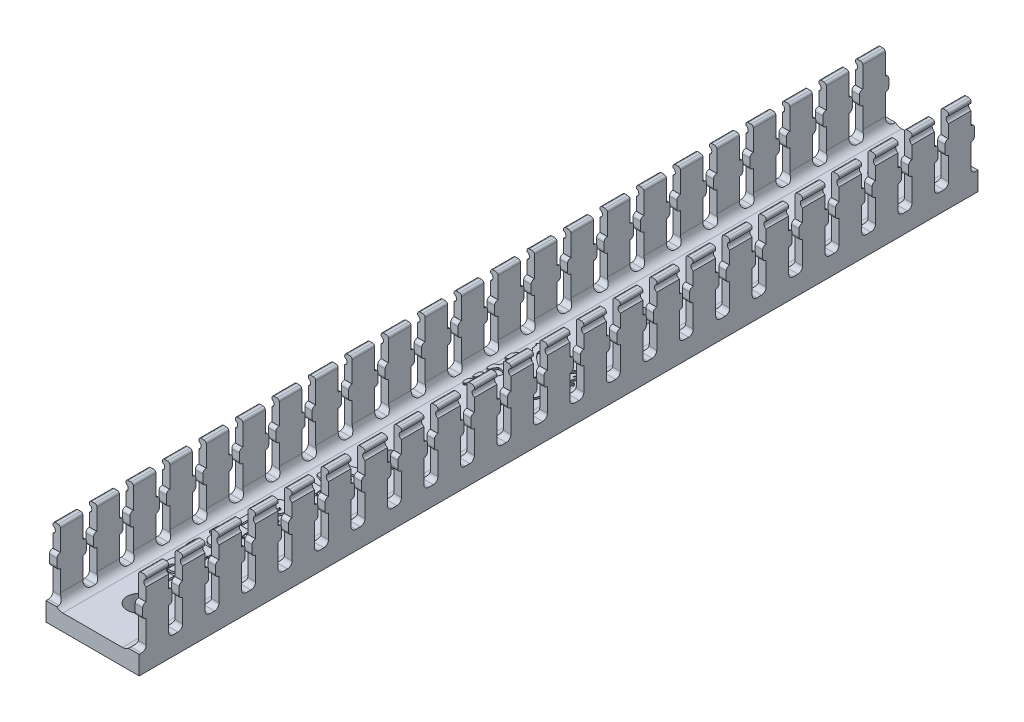
SolidWorks part; units mm, degrees
ref_plane "Front Plane" through (0, 0, 0) normal (0, 0, 1) x (1, 0, 0)
ref_plane "Top Plane" through (0, 0, 0) normal (0, 1, 0) x (1, 0, 0)
ref_plane "Right Plane" through (0, 0, 0) normal (1, 0, 0) x (0, 0, -1)
sketch "Sketch1" plane through (0, 0, 0) normal (0, 0, 1) x (1, 0, 0)
  line L0 (18.9, 18) -> (19.5, 18)
  line L1 (0, 0) -> (20, 0)
  line L2 (0, 0) -> (0, 15.7929)
  line L3 (0.5, 18) -> (1.1, 18)
  line L4 (20, 0) -> (20, 15.7929)
  line L6 (1.6, 17.5) -> (1.6, 5.5)
  line L7 (3.6, 3.5) -> (16.4, 3.5)
  line L8 (18.4, 17.5) -> (18.4, 5.5)
  line L9 (-0.25, 16.5) -> (20.25, 16.5) construction
  line L10 (0, 17.2071) -> (0, 17.5)
  line L11 (20, 17.2071) -> (20, 17.5)
  arc A0 (20, 17.2071) -> (20, 15.7929) centre (20.25, 16.5) ccw
  arc A1 (0, 15.7929) -> (0, 17.2071) centre (-0.25, 16.5) ccw
  arc A2 (1.6, 17.5) -> (1.1, 18) centre (1.1, 17.5) ccw
  arc A3 (18.4, 17.5) -> (18.9, 18) centre (18.9, 17.5) cw
  arc A4 (20, 17.5) -> (19.5, 18) centre (19.5, 17.5) ccw
  arc A5 (0.5, 18) -> (0, 17.5) centre (0.5, 17.5) ccw
  arc A6 (18.4, 5.5) -> (16.4, 3.5) centre (16.4, 5.5) cw
  arc A7 (3.6, 3.5) -> (1.6, 5.5) centre (3.6, 5.5) cw
  point P9 (10, 0)
  point P10 (10, 3.5)
  point P25 (0, 18)
  point P30 (19.5, 16.5)
  point P31 (0.5, 16.5)
  dimension "D5" = 1.5
  dimension "D7" = 0.5
  dimension "D8" = 2
  dimension "D1" = 20
  dimension "D2" = 18
  dimension "D3" = 3.5
  dimension "D4" = 1.6
  dimension "D6" = 1.5
  dimension "D9" = 0.5
  dimension "D10" = 0.5
extrude "Boss-Extrude1" add sketch "Sketch1" along normal blind 180
sketch "Sketch2" plane through (0, 0, 0) normal (-1, 0, 0) x (0, 0, 1)
  line L0 (180, 18) -> (0, 18) construction
  line L1 (-0.5, 4) -> (0.5, 4)
  line L2 (-1.5, 5) -> (-1.5, 10)
  line L3 (-1.5, 18) -> (1.5, 18)
  line L4 (1.5, 5) -> (1.5, 10)
  line L5 (1.45, 10) -> (1.5, 10)
  line L6 (7.3261, 4) -> (8.3261, 4)
  line L7 (-1.5, 13) -> (-1.5, 18)
  line L12 (1.5, 13) -> (1.5, 18)
  line L15 (-1.5, 13) -> (-1.45, 13)
  line L17 (-0.75, 12.3) -> (-0.75, 10.7)
  line L19 (0.75, 12.3) -> (0.75, 10.7)
  line L21 (-0.75, 11.5) -> (0.75, 11.5) construction
  line L22 (-1.45, 10) -> (-1.5, 10)
  line L23 (1.45, 13) -> (1.5, 13)
  line L24 (0, 15.7929) -> (0, 0) construction
  line L37 (180, 0) -> (0, 0) construction
  line L38 (6.3261, 5) -> (6.3261, 10)
  line L39 (6.3261, 18) -> (9.3261, 18)
  line L40 (9.3261, 5) -> (9.3261, 10)
  line L41 (9.2761, 10) -> (9.3261, 10)
  line L42 (6.3261, 13) -> (6.3261, 18)
  line L43 (9.3261, 13) -> (9.3261, 18)
  line L44 (6.3261, 13) -> (6.3761, 13)
  line L45 (7.0761, 12.3) -> (7.0761, 10.7)
  line L46 (8.5761, 12.3) -> (8.5761, 10.7)
  line L47 (6.3761, 10) -> (6.3261, 10)
  line L48 (9.2761, 13) -> (9.3261, 13)
  line L49 (7.0761, 11.5) -> (8.5761, 11.5) construction
  line L50 (15.1522, 4) -> (16.1522, 4)
  line L51 (14.1522, 5) -> (14.1522, 10)
  line L52 (14.1522, 18) -> (17.1522, 18)
  line L53 (17.1522, 5) -> (17.1522, 10)
  line L54 (17.1022, 10) -> (17.1522, 10)
  line L55 (14.1522, 13) -> (14.1522, 18)
  line L56 (17.1522, 13) -> (17.1522, 18)
  line L57 (14.1522, 13) -> (14.2022, 13)
  line L58 (14.9022, 12.3) -> (14.9022, 10.7)
  line L59 (16.4022, 12.3) -> (16.4022, 10.7)
  line L60 (14.2022, 10) -> (14.1522, 10)
  line L61 (17.1022, 13) -> (17.1522, 13)
  line L62 (14.9022, 11.5) -> (16.4022, 11.5) construction
  line L63 (22.9783, 4) -> (23.9783, 4)
  line L64 (21.9783, 5) -> (21.9783, 10)
  line L65 (21.9783, 18) -> (24.9783, 18)
  line L66 (24.9783, 5) -> (24.9783, 10)
  line L67 (24.9283, 10) -> (24.9783, 10)
  line L68 (21.9783, 13) -> (21.9783, 18)
  line L69 (24.9783, 13) -> (24.9783, 18)
  line L70 (21.9783, 13) -> (22.0283, 13)
  line L71 (22.7283, 12.3) -> (22.7283, 10.7)
  line L72 (24.2283, 12.3) -> (24.2283, 10.7)
  line L73 (22.0283, 10) -> (21.9783, 10)
  line L74 (24.9283, 13) -> (24.9783, 13)
  line L75 (22.7283, 11.5) -> (24.2283, 11.5) construction
  line L76 (30.8043, 4) -> (31.8043, 4)
  line L77 (29.8043, 5) -> (29.8043, 10)
  line L78 (29.8043, 18) -> (32.8043, 18)
  line L79 (32.8043, 5) -> (32.8043, 10)
  line L80 (32.7543, 10) -> (32.8043, 10)
  line L81 (29.8043, 13) -> (29.8043, 18)
  line L82 (32.8043, 13) -> (32.8043, 18)
  line L83 (29.8043, 13) -> (29.8543, 13)
  line L84 (30.5543, 12.3) -> (30.5543, 10.7)
  line L85 (32.0543, 12.3) -> (32.0543, 10.7)
  line L86 (29.8543, 10) -> (29.8043, 10)
  line L87 (32.7543, 13) -> (32.8043, 13)
  line L88 (30.5543, 11.5) -> (32.0543, 11.5) construction
  line L89 (38.6304, 4) -> (39.6304, 4)
  line L90 (37.6304, 5) -> (37.6304, 10)
  line L91 (37.6304, 18) -> (40.6304, 18)
  line L92 (40.6304, 5) -> (40.6304, 10)
  line L93 (40.5804, 10) -> (40.6304, 10)
  line L94 (37.6304, 13) -> (37.6304, 18)
  line L95 (40.6304, 13) -> (40.6304, 18)
  line L96 (37.6304, 13) -> (37.6804, 13)
  line L97 (38.3804, 12.3) -> (38.3804, 10.7)
  line L98 (39.8804, 12.3) -> (39.8804, 10.7)
  line L99 (37.6804, 10) -> (37.6304, 10)
  line L100 (40.5804, 13) -> (40.6304, 13)
  line L101 (38.3804, 11.5) -> (39.8804, 11.5) construction
  line L102 (46.4565, 4) -> (47.4565, 4)
  line L103 (45.4565, 5) -> (45.4565, 10)
  line L104 (45.4565, 18) -> (48.4565, 18)
  line L105 (48.4565, 5) -> (48.4565, 10)
  line L106 (48.4065, 10) -> (48.4565, 10)
  line L107 (45.4565, 13) -> (45.4565, 18)
  line L108 (48.4565, 13) -> (48.4565, 18)
  line L109 (45.4565, 13) -> (45.5065, 13)
  line L110 (46.2065, 12.3) -> (46.2065, 10.7)
  line L111 (47.7065, 12.3) -> (47.7065, 10.7)
  line L112 (45.5065, 10) -> (45.4565, 10)
  line L113 (48.4065, 13) -> (48.4565, 13)
  line L114 (46.2065, 11.5) -> (47.7065, 11.5) construction
  line L115 (54.2826, 4) -> (55.2826, 4)
  line L116 (53.2826, 5) -> (53.2826, 10)
  line L117 (53.2826, 18) -> (56.2826, 18)
  line L118 (56.2826, 5) -> (56.2826, 10)
  line L119 (56.2326, 10) -> (56.2826, 10)
  line L120 (53.2826, 13) -> (53.2826, 18)
  line L121 (56.2826, 13) -> (56.2826, 18)
  line L122 (53.2826, 13) -> (53.3326, 13)
  line L123 (54.0326, 12.3) -> (54.0326, 10.7)
  line L124 (55.5326, 12.3) -> (55.5326, 10.7)
  line L125 (53.3326, 10) -> (53.2826, 10)
  line L126 (56.2326, 13) -> (56.2826, 13)
  line L127 (54.0326, 11.5) -> (55.5326, 11.5) construction
  line L128 (62.1087, 4) -> (63.1087, 4)
  line L129 (61.1087, 5) -> (61.1087, 10)
  line L130 (61.1087, 18) -> (64.1087, 18)
  line L131 (64.1087, 5) -> (64.1087, 10)
  line L132 (64.0587, 10) -> (64.1087, 10)
  line L133 (61.1087, 13) -> (61.1087, 18)
  line L134 (64.1087, 13) -> (64.1087, 18)
  line L135 (61.1087, 13) -> (61.1587, 13)
  line L136 (61.8587, 12.3) -> (61.8587, 10.7)
  line L137 (63.3587, 12.3) -> (63.3587, 10.7)
  line L138 (61.1587, 10) -> (61.1087, 10)
  line L139 (64.0587, 13) -> (64.1087, 13)
  line L140 (61.8587, 11.5) -> (63.3587, 11.5) construction
  line L141 (69.9348, 4) -> (70.9348, 4)
  line L142 (68.9348, 5) -> (68.9348, 10)
  line L143 (68.9348, 18) -> (71.9348, 18)
  line L144 (71.9348, 5) -> (71.9348, 10)
  line L145 (71.8848, 10) -> (71.9348, 10)
  line L146 (68.9348, 13) -> (68.9348, 18)
  line L147 (71.9348, 13) -> (71.9348, 18)
  line L148 (68.9348, 13) -> (68.9848, 13)
  line L149 (69.6848, 12.3) -> (69.6848, 10.7)
  line L150 (71.1848, 12.3) -> (71.1848, 10.7)
  line L151 (68.9848, 10) -> (68.9348, 10)
  line L152 (71.8848, 13) -> (71.9348, 13)
  line L153 (69.6848, 11.5) -> (71.1848, 11.5) construction
  line L154 (77.7609, 4) -> (78.7609, 4)
  line L155 (76.7609, 5) -> (76.7609, 10)
  line L156 (76.7609, 18) -> (79.7609, 18)
  line L157 (79.7609, 5) -> (79.7609, 10)
  line L158 (79.7109, 10) -> (79.7609, 10)
  line L159 (76.7609, 13) -> (76.7609, 18)
  line L160 (79.7609, 13) -> (79.7609, 18)
  line L161 (76.7609, 13) -> (76.8109, 13)
  line L162 (77.5109, 12.3) -> (77.5109, 10.7)
  line L163 (79.0109, 12.3) -> (79.0109, 10.7)
  line L164 (76.8109, 10) -> (76.7609, 10)
  line L165 (79.7109, 13) -> (79.7609, 13)
  line L166 (77.5109, 11.5) -> (79.0109, 11.5) construction
  line L167 (85.587, 4) -> (86.587, 4)
  line L168 (84.587, 5) -> (84.587, 10)
  line L169 (84.587, 18) -> (87.587, 18)
  line L170 (87.587, 5) -> (87.587, 10)
  line L171 (87.537, 10) -> (87.587, 10)
  line L172 (84.587, 13) -> (84.587, 18)
  line L173 (87.587, 13) -> (87.587, 18)
  line L174 (84.587, 13) -> (84.637, 13)
  line L175 (85.337, 12.3) -> (85.337, 10.7)
  line L176 (86.837, 12.3) -> (86.837, 10.7)
  line L177 (84.637, 10) -> (84.587, 10)
  line L178 (87.537, 13) -> (87.587, 13)
  line L179 (85.337, 11.5) -> (86.837, 11.5) construction
  line L180 (93.413, 4) -> (94.413, 4)
  line L181 (92.413, 5) -> (92.413, 10)
  line L182 (92.413, 18) -> (95.413, 18)
  line L183 (95.413, 5) -> (95.413, 10)
  line L184 (95.363, 10) -> (95.413, 10)
  line L185 (92.413, 13) -> (92.413, 18)
  line L186 (95.413, 13) -> (95.413, 18)
  line L187 (92.413, 13) -> (92.463, 13)
  line L188 (93.163, 12.3) -> (93.163, 10.7)
  line L189 (94.663, 12.3) -> (94.663, 10.7)
  line L190 (92.463, 10) -> (92.413, 10)
  line L191 (95.363, 13) -> (95.413, 13)
  line L192 (93.163, 11.5) -> (94.663, 11.5) construction
  line L193 (101.2391, 4) -> (102.2391, 4)
  line L194 (100.2391, 5) -> (100.2391, 10)
  line L195 (100.2391, 18) -> (103.2391, 18)
  line L196 (103.2391, 5) -> (103.2391, 10)
  line L197 (103.1891, 10) -> (103.2391, 10)
  line L198 (100.2391, 13) -> (100.2391, 18)
  line L199 (103.2391, 13) -> (103.2391, 18)
  line L200 (100.2391, 13) -> (100.2891, 13)
  line L201 (100.9891, 12.3) -> (100.9891, 10.7)
  line L202 (102.4891, 12.3) -> (102.4891, 10.7)
  line L203 (100.2891, 10) -> (100.2391, 10)
  line L204 (103.1891, 13) -> (103.2391, 13)
  line L205 (100.9891, 11.5) -> (102.4891, 11.5) construction
  line L206 (109.0652, 4) -> (110.0652, 4)
  line L207 (108.0652, 5) -> (108.0652, 10)
  line L208 (108.0652, 18) -> (111.0652, 18)
  line L209 (111.0652, 5) -> (111.0652, 10)
  line L210 (111.0152, 10) -> (111.0652, 10)
  line L211 (108.0652, 13) -> (108.0652, 18)
  line L212 (111.0652, 13) -> (111.0652, 18)
  line L213 (108.0652, 13) -> (108.1152, 13)
  line L214 (108.8152, 12.3) -> (108.8152, 10.7)
  line L215 (110.3152, 12.3) -> (110.3152, 10.7)
  line L216 (108.1152, 10) -> (108.0652, 10)
  line L217 (111.0152, 13) -> (111.0652, 13)
  line L218 (108.8152, 11.5) -> (110.3152, 11.5) construction
  line L219 (116.8913, 4) -> (117.8913, 4)
  line L220 (115.8913, 5) -> (115.8913, 10)
  line L221 (115.8913, 18) -> (118.8913, 18)
  line L222 (118.8913, 5) -> (118.8913, 10)
  line L223 (118.8413, 10) -> (118.8913, 10)
  line L224 (115.8913, 13) -> (115.8913, 18)
  line L225 (118.8913, 13) -> (118.8913, 18)
  line L226 (115.8913, 13) -> (115.9413, 13)
  line L227 (116.6413, 12.3) -> (116.6413, 10.7)
  line L228 (118.1413, 12.3) -> (118.1413, 10.7)
  line L229 (115.9413, 10) -> (115.8913, 10)
  line L230 (118.8413, 13) -> (118.8913, 13)
  line L231 (116.6413, 11.5) -> (118.1413, 11.5) construction
  line L232 (124.7174, 4) -> (125.7174, 4)
  line L233 (123.7174, 5) -> (123.7174, 10)
  line L234 (123.7174, 18) -> (126.7174, 18)
  line L235 (126.7174, 5) -> (126.7174, 10)
  line L236 (126.6674, 10) -> (126.7174, 10)
  line L237 (123.7174, 13) -> (123.7174, 18)
  line L238 (126.7174, 13) -> (126.7174, 18)
  line L239 (123.7174, 13) -> (123.7674, 13)
  line L240 (124.4674, 12.3) -> (124.4674, 10.7)
  line L241 (125.9674, 12.3) -> (125.9674, 10.7)
  line L242 (123.7674, 10) -> (123.7174, 10)
  line L243 (126.6674, 13) -> (126.7174, 13)
  line L244 (124.4674, 11.5) -> (125.9674, 11.5) construction
  line L245 (132.5435, 4) -> (133.5435, 4)
  line L246 (131.5435, 5) -> (131.5435, 10)
  line L247 (131.5435, 18) -> (134.5435, 18)
  line L248 (134.5435, 5) -> (134.5435, 10)
  line L249 (134.4935, 10) -> (134.5435, 10)
  line L250 (131.5435, 13) -> (131.5435, 18)
  line L251 (134.5435, 13) -> (134.5435, 18)
  line L252 (131.5435, 13) -> (131.5935, 13)
  line L253 (132.2935, 12.3) -> (132.2935, 10.7)
  line L254 (133.7935, 12.3) -> (133.7935, 10.7)
  line L255 (131.5935, 10) -> (131.5435, 10)
  line L256 (134.4935, 13) -> (134.5435, 13)
  line L257 (132.2935, 11.5) -> (133.7935, 11.5) construction
  line L258 (140.3696, 4) -> (141.3696, 4)
  line L259 (139.3696, 5) -> (139.3696, 10)
  line L260 (139.3696, 18) -> (142.3696, 18)
  line L261 (142.3696, 5) -> (142.3696, 10)
  line L262 (142.3196, 10) -> (142.3696, 10)
  line L263 (139.3696, 13) -> (139.3696, 18)
  line L264 (142.3696, 13) -> (142.3696, 18)
  line L265 (139.3696, 13) -> (139.4196, 13)
  line L266 (140.1196, 12.3) -> (140.1196, 10.7)
  line L267 (141.6196, 12.3) -> (141.6196, 10.7)
  line L268 (139.4196, 10) -> (139.3696, 10)
  line L269 (142.3196, 13) -> (142.3696, 13)
  line L270 (140.1196, 11.5) -> (141.6196, 11.5) construction
  line L271 (148.1957, 4) -> (149.1957, 4)
  line L272 (147.1957, 5) -> (147.1957, 10)
  line L273 (147.1957, 18) -> (150.1957, 18)
  line L274 (150.1957, 5) -> (150.1957, 10)
  line L275 (150.1457, 10) -> (150.1957, 10)
  line L276 (147.1957, 13) -> (147.1957, 18)
  line L277 (150.1957, 13) -> (150.1957, 18)
  line L278 (147.1957, 13) -> (147.2457, 13)
  line L279 (147.9457, 12.3) -> (147.9457, 10.7)
  line L280 (149.4457, 12.3) -> (149.4457, 10.7)
  line L281 (147.2457, 10) -> (147.1957, 10)
  line L282 (150.1457, 13) -> (150.1957, 13)
  line L283 (147.9457, 11.5) -> (149.4457, 11.5) construction
  line L284 (156.0217, 4) -> (157.0217, 4)
  line L285 (155.0217, 5) -> (155.0217, 10)
  line L286 (155.0217, 18) -> (158.0217, 18)
  line L287 (158.0217, 5) -> (158.0217, 10)
  line L288 (157.9717, 10) -> (158.0217, 10)
  line L289 (155.0217, 13) -> (155.0217, 18)
  line L290 (158.0217, 13) -> (158.0217, 18)
  line L291 (155.0217, 13) -> (155.0717, 13)
  line L292 (155.7717, 12.3) -> (155.7717, 10.7)
  line L293 (157.2717, 12.3) -> (157.2717, 10.7)
  line L294 (155.0717, 10) -> (155.0217, 10)
  line L295 (157.9717, 13) -> (158.0217, 13)
  line L296 (155.7717, 11.5) -> (157.2717, 11.5) construction
  line L297 (163.8478, 4) -> (164.8478, 4)
  line L298 (162.8478, 5) -> (162.8478, 10)
  line L299 (162.8478, 18) -> (165.8478, 18)
  line L300 (165.8478, 5) -> (165.8478, 10)
  line L301 (165.7978, 10) -> (165.8478, 10)
  line L302 (162.8478, 13) -> (162.8478, 18)
  line L303 (165.8478, 13) -> (165.8478, 18)
  line L304 (162.8478, 13) -> (162.8978, 13)
  line L305 (163.5978, 12.3) -> (163.5978, 10.7)
  line L306 (165.0978, 12.3) -> (165.0978, 10.7)
  line L307 (162.8978, 10) -> (162.8478, 10)
  line L308 (165.7978, 13) -> (165.8478, 13)
  line L309 (163.5978, 11.5) -> (165.0978, 11.5) construction
  line L310 (171.6739, 4) -> (172.6739, 4)
  line L311 (170.6739, 5) -> (170.6739, 10)
  line L312 (170.6739, 18) -> (173.6739, 18)
  line L313 (173.6739, 5) -> (173.6739, 10)
  line L314 (173.6239, 10) -> (173.6739, 10)
  line L315 (170.6739, 13) -> (170.6739, 18)
  line L316 (173.6739, 13) -> (173.6739, 18)
  line L317 (170.6739, 13) -> (170.7239, 13)
  line L318 (171.4239, 12.3) -> (171.4239, 10.7)
  line L319 (172.9239, 12.3) -> (172.9239, 10.7)
  line L320 (170.7239, 10) -> (170.6739, 10)
  line L321 (173.6239, 13) -> (173.6739, 13)
  line L322 (171.4239, 11.5) -> (172.9239, 11.5) construction
  line L323 (179.5, 4) -> (180.5, 4)
  line L324 (178.5, 5) -> (178.5, 10)
  line L325 (178.5, 18) -> (181.5, 18)
  line L326 (181.5, 5) -> (181.5, 10)
  line L327 (181.45, 10) -> (181.5, 10)
  line L328 (178.5, 13) -> (178.5, 18)
  line L329 (181.5, 13) -> (181.5, 18)
  line L330 (178.5, 13) -> (178.55, 13)
  line L331 (179.25, 12.3) -> (179.25, 10.7)
  line L332 (180.75, 12.3) -> (180.75, 10.7)
  line L333 (178.55, 10) -> (178.5, 10)
  line L334 (181.45, 13) -> (181.5, 13)
  line L335 (179.25, 11.5) -> (180.75, 11.5) construction
  line L336 (180, 15.7929) -> (180, 0) construction
  arc A0 (-0.5, 4) -> (-1.5, 5) centre (-0.5, 5) cw
  arc A1 (0.5, 4) -> (1.5, 5) centre (0.5, 5) ccw
  arc A2 (-1.45, 13) -> (-0.75, 12.3) centre (-1.45, 12.3) cw
  arc A3 (-1.45, 10) -> (-0.75, 10.7) centre (-1.45, 10.7) ccw
  arc A4 (1.45, 10) -> (0.75, 10.7) centre (1.45, 10.7) cw
  arc A5 (1.45, 13) -> (0.75, 12.3) centre (1.45, 12.3) ccw
  arc A6 (7.3261, 4) -> (6.3261, 5) centre (7.3261, 5) cw
  arc A7 (8.3261, 4) -> (9.3261, 5) centre (8.3261, 5) ccw
  arc A8 (6.3761, 13) -> (7.0761, 12.3) centre (6.3761, 12.3) cw
  arc A9 (6.3761, 10) -> (7.0761, 10.7) centre (6.3761, 10.7) ccw
  arc A10 (9.2761, 10) -> (8.5761, 10.7) centre (9.2761, 10.7) cw
  arc A11 (9.2761, 13) -> (8.5761, 12.3) centre (9.2761, 12.3) ccw
  arc A12 (15.1522, 4) -> (14.1522, 5) centre (15.1522, 5) cw
  arc A13 (16.1522, 4) -> (17.1522, 5) centre (16.1522, 5) ccw
  arc A14 (14.2022, 13) -> (14.9022, 12.3) centre (14.2022, 12.3) cw
  arc A15 (14.2022, 10) -> (14.9022, 10.7) centre (14.2022, 10.7) ccw
  arc A16 (17.1022, 10) -> (16.4022, 10.7) centre (17.1022, 10.7) cw
  arc A17 (17.1022, 13) -> (16.4022, 12.3) centre (17.1022, 12.3) ccw
  arc A18 (22.9783, 4) -> (21.9783, 5) centre (22.9783, 5) cw
  arc A19 (23.9783, 4) -> (24.9783, 5) centre (23.9783, 5) ccw
  arc A20 (22.0283, 13) -> (22.7283, 12.3) centre (22.0283, 12.3) cw
  arc A21 (22.0283, 10) -> (22.7283, 10.7) centre (22.0283, 10.7) ccw
  arc A22 (24.9283, 10) -> (24.2283, 10.7) centre (24.9283, 10.7) cw
  arc A23 (24.9283, 13) -> (24.2283, 12.3) centre (24.9283, 12.3) ccw
  arc A24 (30.8043, 4) -> (29.8043, 5) centre (30.8043, 5) cw
  arc A25 (31.8043, 4) -> (32.8043, 5) centre (31.8043, 5) ccw
  arc A26 (29.8543, 13) -> (30.5543, 12.3) centre (29.8543, 12.3) cw
  arc A27 (29.8543, 10) -> (30.5543, 10.7) centre (29.8543, 10.7) ccw
  arc A28 (32.7543, 10) -> (32.0543, 10.7) centre (32.7543, 10.7) cw
  arc A29 (32.7543, 13) -> (32.0543, 12.3) centre (32.7543, 12.3) ccw
  arc A30 (38.6304, 4) -> (37.6304, 5) centre (38.6304, 5) cw
  arc A31 (39.6304, 4) -> (40.6304, 5) centre (39.6304, 5) ccw
  arc A32 (37.6804, 13) -> (38.3804, 12.3) centre (37.6804, 12.3) cw
  arc A33 (37.6804, 10) -> (38.3804, 10.7) centre (37.6804, 10.7) ccw
  arc A34 (40.5804, 10) -> (39.8804, 10.7) centre (40.5804, 10.7) cw
  arc A35 (40.5804, 13) -> (39.8804, 12.3) centre (40.5804, 12.3) ccw
  arc A36 (46.4565, 4) -> (45.4565, 5) centre (46.4565, 5) cw
  arc A37 (47.4565, 4) -> (48.4565, 5) centre (47.4565, 5) ccw
  arc A38 (45.5065, 13) -> (46.2065, 12.3) centre (45.5065, 12.3) cw
  arc A39 (45.5065, 10) -> (46.2065, 10.7) centre (45.5065, 10.7) ccw
  arc A40 (48.4065, 10) -> (47.7065, 10.7) centre (48.4065, 10.7) cw
  arc A41 (48.4065, 13) -> (47.7065, 12.3) centre (48.4065, 12.3) ccw
  arc A42 (54.2826, 4) -> (53.2826, 5) centre (54.2826, 5) cw
  arc A43 (55.2826, 4) -> (56.2826, 5) centre (55.2826, 5) ccw
  arc A44 (53.3326, 13) -> (54.0326, 12.3) centre (53.3326, 12.3) cw
  arc A45 (53.3326, 10) -> (54.0326, 10.7) centre (53.3326, 10.7) ccw
  arc A46 (56.2326, 10) -> (55.5326, 10.7) centre (56.2326, 10.7) cw
  arc A47 (56.2326, 13) -> (55.5326, 12.3) centre (56.2326, 12.3) ccw
  arc A48 (62.1087, 4) -> (61.1087, 5) centre (62.1087, 5) cw
  arc A49 (63.1087, 4) -> (64.1087, 5) centre (63.1087, 5) ccw
  arc A50 (61.1587, 13) -> (61.8587, 12.3) centre (61.1587, 12.3) cw
  arc A51 (61.1587, 10) -> (61.8587, 10.7) centre (61.1587, 10.7) ccw
  arc A52 (64.0587, 10) -> (63.3587, 10.7) centre (64.0587, 10.7) cw
  arc A53 (64.0587, 13) -> (63.3587, 12.3) centre (64.0587, 12.3) ccw
  arc A54 (69.9348, 4) -> (68.9348, 5) centre (69.9348, 5) cw
  arc A55 (70.9348, 4) -> (71.9348, 5) centre (70.9348, 5) ccw
  arc A56 (68.9848, 13) -> (69.6848, 12.3) centre (68.9848, 12.3) cw
  arc A57 (68.9848, 10) -> (69.6848, 10.7) centre (68.9848, 10.7) ccw
  arc A58 (71.8848, 10) -> (71.1848, 10.7) centre (71.8848, 10.7) cw
  arc A59 (71.8848, 13) -> (71.1848, 12.3) centre (71.8848, 12.3) ccw
  arc A60 (77.7609, 4) -> (76.7609, 5) centre (77.7609, 5) cw
  arc A61 (78.7609, 4) -> (79.7609, 5) centre (78.7609, 5) ccw
  arc A62 (76.8109, 13) -> (77.5109, 12.3) centre (76.8109, 12.3) cw
  arc A63 (76.8109, 10) -> (77.5109, 10.7) centre (76.8109, 10.7) ccw
  arc A64 (79.7109, 10) -> (79.0109, 10.7) centre (79.7109, 10.7) cw
  arc A65 (79.7109, 13) -> (79.0109, 12.3) centre (79.7109, 12.3) ccw
  arc A66 (85.587, 4) -> (84.587, 5) centre (85.587, 5) cw
  arc A67 (86.587, 4) -> (87.587, 5) centre (86.587, 5) ccw
  arc A68 (84.637, 13) -> (85.337, 12.3) centre (84.637, 12.3) cw
  arc A69 (84.637, 10) -> (85.337, 10.7) centre (84.637, 10.7) ccw
  arc A70 (87.537, 10) -> (86.837, 10.7) centre (87.537, 10.7) cw
  arc A71 (87.537, 13) -> (86.837, 12.3) centre (87.537, 12.3) ccw
  arc A72 (93.413, 4) -> (92.413, 5) centre (93.413, 5) cw
  arc A73 (94.413, 4) -> (95.413, 5) centre (94.413, 5) ccw
  arc A74 (92.463, 13) -> (93.163, 12.3) centre (92.463, 12.3) cw
  arc A75 (92.463, 10) -> (93.163, 10.7) centre (92.463, 10.7) ccw
  arc A76 (95.363, 10) -> (94.663, 10.7) centre (95.363, 10.7) cw
  arc A77 (95.363, 13) -> (94.663, 12.3) centre (95.363, 12.3) ccw
  arc A78 (101.2391, 4) -> (100.2391, 5) centre (101.2391, 5) cw
  arc A79 (102.2391, 4) -> (103.2391, 5) centre (102.2391, 5) ccw
  arc A80 (100.2891, 13) -> (100.9891, 12.3) centre (100.2891, 12.3) cw
  arc A81 (100.2891, 10) -> (100.9891, 10.7) centre (100.2891, 10.7) ccw
  arc A82 (103.1891, 10) -> (102.4891, 10.7) centre (103.1891, 10.7) cw
  arc A83 (103.1891, 13) -> (102.4891, 12.3) centre (103.1891, 12.3) ccw
  arc A84 (109.0652, 4) -> (108.0652, 5) centre (109.0652, 5) cw
  arc A85 (110.0652, 4) -> (111.0652, 5) centre (110.0652, 5) ccw
  arc A86 (108.1152, 13) -> (108.8152, 12.3) centre (108.1152, 12.3) cw
  arc A87 (108.1152, 10) -> (108.8152, 10.7) centre (108.1152, 10.7) ccw
  arc A88 (111.0152, 10) -> (110.3152, 10.7) centre (111.0152, 10.7) cw
  arc A89 (111.0152, 13) -> (110.3152, 12.3) centre (111.0152, 12.3) ccw
  arc A90 (116.8913, 4) -> (115.8913, 5) centre (116.8913, 5) cw
  arc A91 (117.8913, 4) -> (118.8913, 5) centre (117.8913, 5) ccw
  arc A92 (115.9413, 13) -> (116.6413, 12.3) centre (115.9413, 12.3) cw
  arc A93 (115.9413, 10) -> (116.6413, 10.7) centre (115.9413, 10.7) ccw
  arc A94 (118.8413, 10) -> (118.1413, 10.7) centre (118.8413, 10.7) cw
  arc A95 (118.8413, 13) -> (118.1413, 12.3) centre (118.8413, 12.3) ccw
  arc A96 (124.7174, 4) -> (123.7174, 5) centre (124.7174, 5) cw
  arc A97 (125.7174, 4) -> (126.7174, 5) centre (125.7174, 5) ccw
  arc A98 (123.7674, 13) -> (124.4674, 12.3) centre (123.7674, 12.3) cw
  arc A99 (123.7674, 10) -> (124.4674, 10.7) centre (123.7674, 10.7) ccw
  arc A100 (126.6674, 10) -> (125.9674, 10.7) centre (126.6674, 10.7) cw
  arc A101 (126.6674, 13) -> (125.9674, 12.3) centre (126.6674, 12.3) ccw
  arc A102 (132.5435, 4) -> (131.5435, 5) centre (132.5435, 5) cw
  arc A103 (133.5435, 4) -> (134.5435, 5) centre (133.5435, 5) ccw
  arc A104 (131.5935, 13) -> (132.2935, 12.3) centre (131.5935, 12.3) cw
  arc A105 (131.5935, 10) -> (132.2935, 10.7) centre (131.5935, 10.7) ccw
  arc A106 (134.4935, 10) -> (133.7935, 10.7) centre (134.4935, 10.7) cw
  arc A107 (134.4935, 13) -> (133.7935, 12.3) centre (134.4935, 12.3) ccw
  arc A108 (140.3696, 4) -> (139.3696, 5) centre (140.3696, 5) cw
  arc A109 (141.3696, 4) -> (142.3696, 5) centre (141.3696, 5) ccw
  arc A110 (139.4196, 13) -> (140.1196, 12.3) centre (139.4196, 12.3) cw
  arc A111 (139.4196, 10) -> (140.1196, 10.7) centre (139.4196, 10.7) ccw
  arc A112 (142.3196, 10) -> (141.6196, 10.7) centre (142.3196, 10.7) cw
  arc A113 (142.3196, 13) -> (141.6196, 12.3) centre (142.3196, 12.3) ccw
  arc A114 (148.1957, 4) -> (147.1957, 5) centre (148.1957, 5) cw
  arc A115 (149.1957, 4) -> (150.1957, 5) centre (149.1957, 5) ccw
  arc A116 (147.2457, 13) -> (147.9457, 12.3) centre (147.2457, 12.3) cw
  arc A117 (147.2457, 10) -> (147.9457, 10.7) centre (147.2457, 10.7) ccw
  arc A118 (150.1457, 10) -> (149.4457, 10.7) centre (150.1457, 10.7) cw
  arc A119 (150.1457, 13) -> (149.4457, 12.3) centre (150.1457, 12.3) ccw
  arc A120 (156.0217, 4) -> (155.0217, 5) centre (156.0217, 5) cw
  arc A121 (157.0217, 4) -> (158.0217, 5) centre (157.0217, 5) ccw
  arc A122 (155.0717, 13) -> (155.7717, 12.3) centre (155.0717, 12.3) cw
  arc A123 (155.0717, 10) -> (155.7717, 10.7) centre (155.0717, 10.7) ccw
  arc A124 (157.9717, 10) -> (157.2717, 10.7) centre (157.9717, 10.7) cw
  arc A125 (157.9717, 13) -> (157.2717, 12.3) centre (157.9717, 12.3) ccw
  arc A126 (163.8478, 4) -> (162.8478, 5) centre (163.8478, 5) cw
  arc A127 (164.8478, 4) -> (165.8478, 5) centre (164.8478, 5) ccw
  arc A128 (162.8978, 13) -> (163.5978, 12.3) centre (162.8978, 12.3) cw
  arc A129 (162.8978, 10) -> (163.5978, 10.7) centre (162.8978, 10.7) ccw
  arc A130 (165.7978, 10) -> (165.0978, 10.7) centre (165.7978, 10.7) cw
  arc A131 (165.7978, 13) -> (165.0978, 12.3) centre (165.7978, 12.3) ccw
  arc A132 (171.6739, 4) -> (170.6739, 5) centre (171.6739, 5) cw
  arc A133 (172.6739, 4) -> (173.6739, 5) centre (172.6739, 5) ccw
  arc A134 (170.7239, 13) -> (171.4239, 12.3) centre (170.7239, 12.3) cw
  arc A135 (170.7239, 10) -> (171.4239, 10.7) centre (170.7239, 10.7) ccw
  arc A136 (173.6239, 10) -> (172.9239, 10.7) centre (173.6239, 10.7) cw
  arc A137 (173.6239, 13) -> (172.9239, 12.3) centre (173.6239, 12.3) ccw
  arc A138 (179.5, 4) -> (178.5, 5) centre (179.5, 5) cw
  arc A139 (180.5, 4) -> (181.5, 5) centre (180.5, 5) ccw
  arc A140 (178.55, 13) -> (179.25, 12.3) centre (178.55, 12.3) cw
  arc A141 (178.55, 10) -> (179.25, 10.7) centre (178.55, 10.7) ccw
  arc A142 (181.45, 10) -> (180.75, 10.7) centre (181.45, 10.7) cw
  arc A143 (181.45, 13) -> (180.75, 12.3) centre (181.45, 12.3) ccw
  point P18 (0, 11.5)
  point P19 (0, 18)
  point P26 (0.75, 10)
  point P29 (0.75, 13)
  point P34 (0, 4)
  point P35 (180, 18)
  dimension "D4" = 1
  dimension "D7" = 24
  dimension "D5" = 0.7
  dimension "D1" = 3
  dimension "D2" = 1.5
  dimension "D3" = 4
  dimension "D6" = 3
extrude "Cut-Extrude1" cut sketch "Sketch2" against normal through all
sketch "Sketch3" plane through (0, 3.5, 0) normal (0, 1, 0) x (1, 0, 0)
  line L0 (10, 0) -> (10, -180) construction
  line L1 (16.4, 0) -> (3.6, 0) construction
  line L2 (16.4, -180) -> (3.6, -180) construction
  circle A0 centre (10, -10) radius 2.6
  circle A1 centre (10, -63.3333) radius 2.6
  circle A2 centre (10, -116.6667) radius 2.6
  circle A3 centre (10, -170) radius 2.6
  dimension "D2" = 5.2
  dimension "D4" = 10
  dimension "D1" = 10
  dimension "D3" = 4
extrude "Cut-Extrude2" cut sketch "Sketch3" against normal through all
sketch "Sketch5" plane through (2.4395, 3.5, 15.2169) normal (0, 1, 0) x (1, 0, 0)
  line L4 (13.7789, -67.5816) -> (13.7299, -67.5984)
  line L5 (13.7299, -67.5984) -> (13.6821, -67.6171)
  line L6 (13.6821, -67.6171) -> (13.6354, -67.6375)
  line L7 (13.6354, -67.6375) -> (13.5897, -67.6596)
  line L8 (13.5897, -67.6596) -> (13.545, -67.6832)
  line L9 (13.545, -67.6832) -> (13.5012, -67.7084)
  line L10 (13.5012, -67.7084) -> (13.4584, -67.7351)
  line L11 (13.4584, -67.7351) -> (13.4164, -67.7631)
  line L12 (13.4164, -67.7631) -> (13.3753, -67.7923)
  line L13 (13.3753, -67.7923) -> (13.3349, -67.8228)
  line L14 (13.3349, -67.8228) -> (13.2953, -67.8543)
  line L15 (13.2953, -67.8543) -> (13.2564, -67.8869)
  line L16 (13.2564, -67.8869) -> (13.2182, -67.9204)
  line L17 (13.2182, -67.9204) -> (13.1435, -67.9898)
  line L18 (13.1435, -67.9898) -> (13.0353, -68.099)
  line L19 (13.0353, -68.099) -> (12.6607, -68.5163)
  line L20 (12.6607, -68.5163) -> (12.6692, -68.4281)
  line L21 (12.6692, -68.4281) -> (12.8582, -67.2487)
  line L22 (12.8582, -67.2487) -> (12.8649, -67.2043)
  line L23 (12.8649, -67.2043) -> (12.8729, -67.1603)
  line L24 (12.8729, -67.1603) -> (12.8821, -67.1167)
  line L25 (12.8821, -67.1167) -> (12.8923, -67.0734)
  line L26 (12.8923, -67.0734) -> (12.9159, -66.9879)
  line L27 (12.9159, -66.9879) -> (12.9431, -66.9036)
  line L28 (12.9431, -66.9036) -> (12.9894, -66.7789)
  line L29 (12.9894, -66.7789) -> (13.2398, -66.2083)
  line L30 (13.2398, -66.2083) -> (13.3041, -66.0429)
  line L31 (13.3041, -66.0429) -> (13.2615, -66.0504)
  line L32 (13.2615, -66.0504) -> (13.2201, -66.06)
  line L33 (13.2201, -66.06) -> (13.1798, -66.0717)
  line L34 (13.1798, -66.0717) -> (13.1404, -66.0852)
  line L35 (13.1404, -66.0852) -> (13.102, -66.1005)
  line L36 (13.102, -66.1005) -> (13.0645, -66.1176)
  line L37 (13.0645, -66.1176) -> (13.0279, -66.1363)
  line L38 (13.0279, -66.1363) -> (12.9921, -66.1564)
  line L39 (12.9921, -66.1564) -> (12.957, -66.178)
  line L40 (12.957, -66.178) -> (12.9227, -66.2009)
  line L41 (12.9227, -66.2009) -> (12.8891, -66.225)
  line L42 (12.8891, -66.225) -> (12.8561, -66.2501)
  line L43 (12.8561, -66.2501) -> (12.7918, -66.3034)
  line L44 (12.7918, -66.3034) -> (12.7294, -66.3598)
  line L45 (12.7294, -66.3598) -> (12.6092, -66.4789)
  line L46 (12.6092, -66.4789) -> (12.3464, -66.7477)
  line L47 (12.3464, -66.7477) -> (12.3739, -66.629)
  line L48 (12.3739, -66.629) -> (12.4362, -66.3938)
  line L49 (12.4362, -66.3938) -> (12.5073, -66.1613)
  line L50 (12.5073, -66.1613) -> (12.6281, -65.8171)
  line L51 (12.6281, -65.8171) -> (12.9312, -65.0869)
  line L52 (12.9312, -65.0869) -> (12.9062, -65.0896)
  line L53 (12.9062, -65.0896) -> (12.8569, -65.0977)
  line L54 (12.8569, -65.0977) -> (12.8087, -65.1091)
  line L55 (12.8087, -65.1091) -> (12.7615, -65.1237)
  line L56 (12.7615, -65.1237) -> (12.6926, -65.1508)
  line L57 (12.6926, -65.1508) -> (12.626, -65.1837)
  line L58 (12.626, -65.1837) -> (12.5198, -65.2488)
  line L59 (12.5198, -65.2488) -> (12.3066, -65.42)
  line L60 (12.3066, -65.42) -> (11.7666, -66.0125)
  line L61 (11.7666, -66.0125) -> (11.5876, -66.2601)
  line L62 (11.5876, -66.2601) -> (11.3525, -66.569)
  line L63 (11.3525, -66.569) -> (11.5618, -65.6103)
  line L64 (11.5618, -65.6103) -> (11.6718, -65.0349)
  line L65 (11.6718, -65.0349) -> (11.6189, -65.0647)
  line L66 (11.6189, -65.0647) -> (11.5683, -65.0967)
  line L67 (11.5683, -65.0967) -> (11.5199, -65.1308)
  line L68 (11.5199, -65.1308) -> (11.4736, -65.167)
  line L69 (11.4736, -65.167) -> (11.4293, -65.2051)
  line L70 (11.4293, -65.2051) -> (11.3869, -65.245)
  line L71 (11.3869, -65.245) -> (11.3463, -65.2866)
  line L72 (11.3463, -65.2866) -> (11.3074, -65.3298)
  line L73 (11.3074, -65.3298) -> (11.27, -65.3744)
  line L74 (11.27, -65.3744) -> (11.2341, -65.4204)
  line L75 (11.2341, -65.4204) -> (11.1996, -65.4676)
  line L76 (11.1996, -65.4676) -> (11.1663, -65.516)
  line L77 (11.1663, -65.516) -> (11.1341, -65.5653)
  line L78 (11.1341, -65.5653) -> (11.103, -65.6156)
  line L79 (11.103, -65.6156) -> (11.0434, -65.7183)
  line L80 (11.0434, -65.7183) -> (10.9589, -65.8763)
  line L81 (10.9589, -65.8763) -> (10.7425, -66.2987)
  line L82 (10.7425, -66.2987) -> (10.6858, -66.3996)
  line L83 (10.6858, -66.3996) -> (10.6346, -65.9673)
  line L84 (10.6346, -65.9673) -> (10.6148, -65.9797)
  line L85 (10.6148, -65.9797) -> (10.5775, -66.0067)
  line L86 (10.5775, -66.0067) -> (10.543, -66.0364)
  line L87 (10.543, -66.0364) -> (10.5112, -66.0686)
  line L88 (10.5112, -66.0686) -> (10.4819, -66.103)
  line L89 (10.4819, -66.103) -> (10.4421, -66.1581)
  line L90 (10.4421, -66.1581) -> (10.3959, -66.237)
  line L91 (10.3959, -66.237) -> (10.2827, -66.5121)
  line L92 (10.2827, -66.5121) -> (10.2562, -66.5967)
  line L93 (10.2562, -66.5967) -> (9.9922, -67.762)
  line L94 (9.9922, -67.762) -> (9.8348, -67.523)
  line L95 (9.8348, -67.523) -> (9.8129, -67.6476)
  line L96 (9.8129, -67.6476) -> (9.7124, -68.2752)
  line L97 (9.7124, -68.2752) -> (9.683, -68.3986)
  line L98 (9.683, -68.3986) -> (9.6598, -68.4798)
  line L99 (9.6598, -68.4798) -> (9.6331, -68.5602)
  line L100 (9.6331, -68.5602) -> (9.6025, -68.6396)
  line L101 (9.6025, -68.6396) -> (9.5856, -68.6788)
  line L102 (9.5856, -68.6788) -> (9.5675, -68.7177)
  line L103 (9.5675, -68.7177) -> (9.4672, -68.6192)
  line L104 (9.4672, -68.6192) -> (9.3009, -68.7855)
  line L105 (9.3009, -68.7855) -> (9.2403, -68.8759)
  line L106 (9.2403, -68.8759) -> (9.2149, -68.933)
  line L107 (9.2149, -68.933) -> (9.2013, -68.9788)
  line L108 (9.2013, -68.9788) -> (9.1942, -69.0086)
  line L109 (9.1942, -69.0086) -> (9.1772, -69.0982)
  line L110 (9.1772, -69.0982) -> (9.16, -69.2488)
  line L111 (9.16, -69.2488) -> (9.1308, -69.8561)
  line L112 (9.1308, -69.8561) -> (8.9852, -69.7743)
  line L113 (8.9852, -69.7743) -> (8.9614, -69.8353)
  line L114 (8.9614, -69.8353) -> (8.9211, -69.9594)
  line L115 (8.9211, -69.9594) -> (8.8899, -70.0857)
  line L116 (8.8899, -70.0857) -> (8.8629, -70.2461)
  line L117 (8.8629, -70.2461) -> (8.8463, -70.4408)
  line L118 (8.8463, -70.4408) -> (8.8477, -70.7017)
  line L119 (8.8477, -70.7017) -> (8.7094, -70.731)
  line L120 (8.7094, -70.731) -> (8.6765, -70.7524)
  line L121 (8.6765, -70.7524) -> (8.6611, -70.7709)
  line L122 (8.6611, -70.7709) -> (8.6532, -70.7862)
  line L123 (8.6532, -70.7862) -> (8.6474, -70.8041)
  line L124 (8.6474, -70.8041) -> (8.6426, -70.826)
  line L125 (8.6426, -70.826) -> (8.6363, -70.8698)
  line L126 (8.6363, -70.8698) -> (8.634, -70.9134)
  line L127 (8.634, -70.9134) -> (8.6354, -70.9569)
  line L128 (8.6354, -70.9569) -> (8.64, -71.0001)
  line L129 (8.64, -71.0001) -> (8.6573, -71.086)
  line L130 (8.6573, -71.086) -> (8.7779, -71.418)
  line L131 (8.7779, -71.418) -> (8.5596, -71.3368)
  line L132 (8.5596, -71.3368) -> (8.5672, -72.2041)
  line L133 (8.5672, -72.2041) -> (8.5647, -72.2372)
  line L134 (8.5647, -72.2372) -> (8.5608, -72.2699)
  line L135 (8.5608, -72.2699) -> (8.5557, -72.3023)
  line L136 (8.5557, -72.3023) -> (8.5492, -72.3342)
  line L137 (8.5492, -72.3342) -> (8.5416, -72.3658)
  line L138 (8.5416, -72.3658) -> (8.5327, -72.3969)
  line L139 (8.5327, -72.3969) -> (8.5228, -72.4277)
  line L140 (8.5228, -72.4277) -> (8.5117, -72.458)
  line L141 (8.5117, -72.458) -> (8.4995, -72.4879)
  line L142 (8.4995, -72.4879) -> (8.4863, -72.5173)
  line L143 (8.4863, -72.5173) -> (8.457, -72.5749)
  line L144 (8.457, -72.5749) -> (8.4241, -72.6306)
  line L145 (8.4241, -72.6306) -> (8.3878, -72.6845)
  line L146 (8.3878, -72.6845) -> (8.3485, -72.7364)
  line L147 (8.3485, -72.7364) -> (8.3064, -72.7864)
  line L148 (8.3064, -72.7864) -> (8.239, -72.8576)
  line L149 (8.239, -72.8576) -> (8.1672, -72.924)
  line L150 (8.1672, -72.924) -> (8.0921, -72.9855)
  line L151 (8.0921, -72.9855) -> (8.0262, -72.6489)
  line L152 (8.0262, -72.6489) -> (8.0343, -72.5972)
  line L153 (8.0343, -72.5972) -> (8.0439, -72.5459)
  line L154 (8.0439, -72.5459) -> (8.0547, -72.4949)
  line L155 (8.0547, -72.4949) -> (8.0668, -72.4443)
  line L156 (8.0668, -72.4443) -> (8.094, -72.3438)
  line L157 (8.094, -72.3438) -> (8.141, -72.1947)
  line L158 (8.141, -72.1947) -> (8.3307, -71.6529)
  line L159 (8.3307, -71.6529) -> (8.3604, -71.5532)
  line L160 (8.3604, -71.5532) -> (8.3865, -71.4525)
  line L161 (8.3865, -71.4525) -> (8.3979, -71.4018)
  line L162 (8.3979, -71.4018) -> (8.4081, -71.3507)
  line L163 (8.4081, -71.3507) -> (8.4169, -71.2992)
  line L164 (8.4169, -71.2992) -> (8.4242, -71.2474)
  line L165 (8.4242, -71.2474) -> (8.4299, -71.1952)
  line L166 (8.4299, -71.1952) -> (8.4345, -71.152)
  line L167 (8.4345, -71.152) -> (8.4414, -71.0652)
  line L168 (8.4414, -71.0652) -> (8.4449, -70.9782)
  line L169 (8.4449, -70.9782) -> (8.445, -70.891)
  line L170 (8.445, -70.891) -> (8.4417, -70.804)
  line L171 (8.4417, -70.804) -> (8.4349, -70.7171)
  line L172 (8.4349, -70.7171) -> (8.4246, -70.6307)
  line L173 (8.4246, -70.6307) -> (8.4107, -70.5447)
  line L174 (8.4107, -70.5447) -> (8.3932, -70.4595)
  line L175 (8.3932, -70.4595) -> (8.3721, -70.3752)
  line L176 (8.3721, -70.3752) -> (8.3473, -70.2918)
  line L177 (8.3473, -70.2918) -> (8.3188, -70.2097)
  line L178 (8.3188, -70.2097) -> (8.2865, -70.1289)
  line L179 (8.2865, -70.1289) -> (8.2503, -70.0496)
  line L180 (8.2503, -70.0496) -> (8.2103, -69.972)
  line L181 (8.2103, -69.972) -> (8.1061, -69.7832)
  line L182 (8.1061, -69.7832) -> (8.0331, -69.6588)
  line L183 (8.0331, -69.6588) -> (7.9572, -69.536)
  line L184 (7.9572, -69.536) -> (7.8782, -69.415)
  line L185 (7.8782, -69.415) -> (7.796, -69.2962)
  line L186 (7.796, -69.2962) -> (7.7104, -69.18)
  line L187 (7.7104, -69.18) -> (7.6663, -69.1229)
  line L188 (7.6663, -69.1229) -> (7.6214, -69.0665)
  line L189 (7.6214, -69.0665) -> (7.5755, -69.011)
  line L190 (7.5755, -69.011) -> (7.5287, -68.9562)
  line L191 (7.5287, -68.9562) -> (7.4809, -68.9023)
  line L192 (7.4809, -68.9023) -> (7.4322, -68.8494)
  line L193 (7.4322, -68.8494) -> (7.3825, -68.7973)
  line L194 (7.3825, -68.7973) -> (7.3318, -68.7463)
  line L195 (7.3318, -68.7463) -> (7.2801, -68.6963)
  line L196 (7.2801, -68.6963) -> (7.2274, -68.6473)
  line L197 (7.2274, -68.6473) -> (7.1737, -68.5995)
  line L198 (7.1737, -68.5995) -> (7.1189, -68.5528)
  line L199 (7.1189, -68.5528) -> (7.063, -68.5073)
  line L200 (7.063, -68.5073) -> (7.006, -68.463)
  line L201 (7.006, -68.463) -> (6.9479, -68.42)
  line L202 (6.9479, -68.42) -> (6.8886, -68.3782)
  line L203 (6.8886, -68.3782) -> (6.0892, -67.8153)
  line L204 (6.0892, -67.8153) -> (6.0387, -67.7831)
  line L205 (6.0387, -67.7831) -> (5.4077, -67.2803)
  line L206 (5.4077, -67.2803) -> (5.2633, -67.1635)
  line L207 (5.2633, -67.1635) -> (5.1229, -67.0422)
  line L208 (5.1229, -67.0422) -> (4.9416, -66.8739)
  line L209 (4.9416, -66.8739) -> (4.7669, -66.6987)
  line L210 (4.7669, -66.6987) -> (4.5987, -66.5171)
  line L211 (4.5987, -66.5171) -> (4.3972, -66.2824)
  line L212 (4.3972, -66.2824) -> (4.1676, -65.9908)
  line L213 (4.1676, -65.9908) -> (4.0522, -65.8247)
  line L214 (4.0522, -65.8247) -> (4.0126, -65.7405)
  line L215 (4.0126, -65.7405) -> (4.0008, -65.6887)
  line L216 (4.0008, -65.6887) -> (3.9987, -65.6478)
  line L217 (3.9987, -65.6478) -> (3.998, -65.6285)
  line L218 (3.998, -65.6285) -> (3.9986, -65.6094)
  line L219 (3.9986, -65.6094) -> (4.0005, -65.5905)
  line L220 (4.0005, -65.5905) -> (4.0072, -65.5531)
  line L221 (4.0072, -65.5531) -> (4.0174, -65.5163)
  line L222 (4.0174, -65.5163) -> (4.0952, -65.3176)
  line L223 (4.0952, -65.3176) -> (4.1102, -65.2628)
  line L224 (4.1102, -65.2628) -> (4.1159, -65.2258)
  line L225 (4.1159, -65.2258) -> (4.117, -65.207)
  line L226 (4.117, -65.207) -> (4.1169, -65.1881)
  line L227 (4.1169, -65.1881) -> (4.1154, -65.1691)
  line L228 (4.1154, -65.1691) -> (4.1125, -65.1498)
  line L229 (4.1125, -65.1498) -> (4.1079, -65.1303)
  line L230 (4.1079, -65.1303) -> (4.1017, -65.1106)
  line L231 (4.1017, -65.1106) -> (3.8803, -64.4671)
  line L232 (3.8803, -64.4671) -> (3.7591, -64.4955)
  line L233 (3.7591, -64.4955) -> (3.5843, -64.0447)
  line L234 (3.5843, -64.0447) -> (3.4817, -64.1755)
  line L235 (3.4817, -64.1755) -> (3.2391, -63.906)
  line L236 (3.2391, -63.906) -> (3.1508, -64.0302)
  line L237 (3.1508, -64.0302) -> (3.0904, -64.0045)
  line L238 (3.0904, -64.0045) -> (2.8409, -63.9279)
  line L239 (2.8409, -63.9279) -> (2.6688, -63.9049)
  line L240 (2.6688, -63.9049) -> (2.5373, -63.9052)
  line L241 (2.5373, -63.9052) -> (2.5311, -64.0937)
  line L242 (2.5311, -64.0937) -> (2.2598, -64.3553)
  line L243 (2.2598, -64.3553) -> (2.3592, -64.4013)
  line L244 (2.3592, -64.4013) -> (2.5423, -64.4881)
  line L245 (2.5423, -64.4881) -> (2.5858, -64.5193)
  line L246 (2.5858, -64.5193) -> (2.6119, -64.5433)
  line L247 (2.6119, -64.5433) -> (2.6353, -64.5703)
  line L248 (2.6353, -64.5703) -> (2.6459, -64.585)
  line L249 (2.6459, -64.585) -> (2.6557, -64.6006)
  line L250 (2.6557, -64.6006) -> (2.6646, -64.6172)
  line L251 (2.6646, -64.6172) -> (2.6726, -64.6347)
  line L252 (2.6726, -64.6347) -> (2.6796, -64.6533)
  line L253 (2.6796, -64.6533) -> (2.4955, -64.6937)
  line L254 (2.4955, -64.6937) -> (2.5082, -64.7534)
  line L255 (2.5082, -64.7534) -> (2.553, -64.8871)
  line L256 (2.553, -64.8871) -> (2.7453, -65.2182)
  line L257 (2.7453, -65.2182) -> (2.6915, -65.378)
  line L258 (2.6915, -65.378) -> (2.6902, -65.4664)
  line L259 (2.6902, -65.4664) -> (2.7054, -65.4997)
  line L260 (2.7054, -65.4997) -> (2.7511, -65.5777)
  line L261 (2.7511, -65.5777) -> (3.0239, -65.8674)
  line L262 (3.0239, -65.8674) -> (3.0428, -65.8845)
  line L263 (3.0428, -65.8845) -> (3.0963, -65.9386)
  line L264 (3.0963, -65.9386) -> (3.1767, -66.0358)
  line L265 (3.1767, -66.0358) -> (3.4672, -66.4506)
  line L266 (3.4672, -66.4506) -> (3.5193, -66.5204)
  line L267 (3.5193, -66.5204) -> (3.5724, -66.5893)
  line L268 (3.5724, -66.5893) -> (3.6266, -66.6573)
  line L269 (3.6266, -66.6573) -> (3.6817, -66.7243)
  line L270 (3.6817, -66.7243) -> (3.7379, -66.7904)
  line L271 (3.7379, -66.7904) -> (3.7949, -66.8557)
  line L272 (3.7949, -66.8557) -> (3.8529, -66.9202)
  line L273 (3.8529, -66.9202) -> (3.9117, -66.9839)
  line L274 (3.9117, -66.9839) -> (3.9714, -67.0468)
  line L275 (3.9714, -67.0468) -> (4.0929, -67.1704)
  line L276 (4.0929, -67.1704) -> (4.2173, -67.2913)
  line L277 (4.2173, -67.2913) -> (4.3443, -67.4096)
  line L278 (4.3443, -67.4096) -> (4.4734, -67.5257)
  line L279 (4.4734, -67.5257) -> (4.6706, -67.6961)
  line L280 (4.6706, -67.6961) -> (5.2783, -68.187)
  line L281 (5.2783, -68.187) -> (5.3106, -68.218)
  line L282 (5.3106, -68.218) -> (5.3769, -68.2779)
  line L283 (5.3769, -68.2779) -> (5.4798, -68.3632)
  line L284 (5.4798, -68.3632) -> (5.6943, -68.5223)
  line L285 (5.6943, -68.5223) -> (6.2013, -68.8858)
  line L286 (6.2013, -68.8858) -> (6.3039, -68.9718)
  line L287 (6.3039, -68.9718) -> (5.9352, -68.9935)
  line L288 (5.9352, -68.9935) -> (5.849, -68.983)
  line L289 (5.849, -68.983) -> (5.7981, -68.9697)
  line L290 (5.7981, -68.9697) -> (5.6876, -68.8858)
  line L291 (5.6876, -68.8858) -> (4.9397, -68.2648)
  line L292 (4.9397, -68.2648) -> (4.7534, -68.1278)
  line L293 (4.7534, -68.1278) -> (4.7168, -68.1048)
  line L294 (4.7168, -68.1048) -> (4.6796, -68.0843)
  line L295 (4.6796, -68.0843) -> (4.6419, -68.0663)
  line L296 (4.6419, -68.0663) -> (4.6038, -68.0505)
  line L297 (4.6038, -68.0505) -> (4.5652, -68.0369)
  line L298 (4.5652, -68.0369) -> (4.5261, -68.0253)
  line L299 (4.5261, -68.0253) -> (4.4866, -68.0156)
  line L300 (4.4866, -68.0156) -> (4.4468, -68.0078)
  line L301 (4.4468, -68.0078) -> (4.4067, -68.0016)
  line L302 (4.4067, -68.0016) -> (4.3662, -67.997)
  line L303 (4.3662, -67.997) -> (4.3255, -67.9938)
  line L304 (4.3255, -67.9938) -> (4.2845, -67.9919)
  line L305 (4.2845, -67.9919) -> (4.2019, -67.9915)
  line L306 (4.2019, -67.9915) -> (4.077, -67.9976)
  line L307 (4.077, -67.9976) -> (3.6616, -68.0361)
  line L308 (3.6616, -68.0361) -> (3.5805, -68.0397)
  line L309 (3.5805, -68.0397) -> (2.773, -67.9662)
  line L310 (2.773, -67.9662) -> (2.6755, -67.9529)
  line L311 (2.6755, -67.9529) -> (2.3073, -67.8967)
  line L312 (2.3073, -67.8967) -> (2.2336, -67.8956)
  line L313 (2.2336, -67.8956) -> (2.1846, -67.8986)
  line L314 (2.1846, -67.8986) -> (2.1357, -67.9052)
  line L315 (2.1357, -67.9052) -> (2.0869, -67.9157)
  line L316 (2.0869, -67.9157) -> (2.0625, -67.9227)
  line L317 (2.0625, -67.9227) -> (2.0447, -67.9291)
  line L318 (2.0447, -67.9291) -> (2.0277, -67.9364)
  line L319 (2.0277, -67.9364) -> (2.0115, -67.9446)
  line L320 (2.0115, -67.9446) -> (1.9812, -67.9635)
  line L321 (1.9812, -67.9635) -> (1.9534, -67.9852)
  line L322 (1.9534, -67.9852) -> (1.9278, -68.0093)
  line L323 (1.9278, -68.0093) -> (1.8711, -68.0781)
  line L324 (1.8711, -68.0781) -> (1.7178, -68.3017)
  line L325 (1.7178, -68.3017) -> (1.6695, -68.3627)
  line L326 (1.6695, -68.3627) -> (1.4799, -68.5657)
  line L327 (1.4799, -68.5657) -> (1.447, -68.6134)
  line L328 (1.447, -68.6134) -> (1.4286, -68.6472)
  line L329 (1.4286, -68.6472) -> (1.4138, -68.6829)
  line L330 (1.4138, -68.6829) -> (1.4079, -68.7016)
  line L331 (1.4079, -68.7016) -> (1.403, -68.7208)
  line L332 (1.403, -68.7208) -> (1.3993, -68.7406)
  line L333 (1.3993, -68.7406) -> (1.3969, -68.7612)
  line L334 (1.3969, -68.7612) -> (1.3938, -68.8032)
  line L335 (1.3938, -68.8032) -> (1.3943, -69.9813)
  line L336 (1.3943, -69.9813) -> (1.3969, -70.0103)
  line L337 (1.3969, -70.0103) -> (1.4264, -70.1055)
  line L338 (1.4264, -70.1055) -> (1.4603, -70.1534)
  line L339 (1.4603, -70.1534) -> (1.4901, -70.1779)
  line L340 (1.4901, -70.1779) -> (1.5163, -70.1912)
  line L341 (1.5163, -70.1912) -> (1.5459, -70.1993)
  line L342 (1.5459, -70.1993) -> (1.7501, -70.2147)
  line L343 (1.7501, -70.2147) -> (1.8181, -70.2082)
  line L344 (1.8181, -70.2082) -> (1.867, -70.1969)
  line L345 (1.867, -70.1969) -> (1.8981, -70.1856)
  line L346 (1.8981, -70.1856) -> (1.9278, -70.171)
  line L347 (1.9278, -70.171) -> (1.9557, -70.1528)
  line L348 (1.9557, -70.1528) -> (1.969, -70.1422)
  line L349 (1.969, -70.1422) -> (1.9817, -70.1306)
  line L350 (1.9817, -70.1306) -> (1.9939, -70.1179)
  line L351 (1.9939, -70.1179) -> (2.0055, -70.1041)
  line L352 (2.0055, -70.1041) -> (2.0264, -70.0818)
  line L353 (2.0264, -70.0818) -> (2.0461, -70.0589)
  line L354 (2.0461, -70.0589) -> (2.0647, -70.0352)
  line L355 (2.0647, -70.0352) -> (2.0822, -70.0109)
  line L356 (2.0822, -70.0109) -> (2.0985, -69.986)
  line L357 (2.0985, -69.986) -> (2.1136, -69.9605)
  line L358 (2.1136, -69.9605) -> (2.1277, -69.9344)
  line L359 (2.1277, -69.9344) -> (2.1407, -69.9078)
  line L360 (2.1407, -69.9078) -> (2.1525, -69.8807)
  line L361 (2.1525, -69.8807) -> (2.1633, -69.8532)
  line L362 (2.1633, -69.8532) -> (2.1729, -69.8253)
  line L363 (2.1729, -69.8253) -> (2.1815, -69.797)
  line L364 (2.1815, -69.797) -> (2.189, -69.7684)
  line L365 (2.189, -69.7684) -> (2.1954, -69.7396)
  line L366 (2.1954, -69.7396) -> (2.2008, -69.7104)
  line L367 (2.2008, -69.7104) -> (2.2084, -69.6516)
  line L368 (2.2084, -69.6516) -> (2.2118, -69.5922)
  line L369 (2.2118, -69.5922) -> (2.2112, -69.5326)
  line L370 (2.2112, -69.5326) -> (2.2066, -69.473)
  line L371 (2.2066, -69.473) -> (2.198, -69.4138)
  line L372 (2.198, -69.4138) -> (2.1854, -69.3553)
  line L373 (2.1854, -69.3553) -> (2.1691, -69.2977)
  line L374 (2.1691, -69.2977) -> (2.6227, -69.095)
  line L375 (2.6227, -69.095) -> (2.9461, -69.3171)
  line L376 (2.9461, -69.3171) -> (3.1327, -69.4214)
  line L377 (3.1327, -69.4214) -> (3.2618, -69.4814)
  line L378 (3.2618, -69.4814) -> (3.3612, -69.5204)
  line L379 (3.3612, -69.5204) -> (3.463, -69.5536)
  line L380 (3.463, -69.5536) -> (3.5322, -69.5723)
  line L381 (3.5322, -69.5723) -> (3.8522, -69.6578)
  line L382 (3.8522, -69.6578) -> (4.0302, -70.1562)
  line L383 (4.0302, -70.1562) -> (4.0452, -70.1971)
  line L384 (4.0452, -70.1971) -> (4.0778, -70.3241)
  line L385 (4.0778, -70.3241) -> (4.1421, -70.6238)
  line L386 (4.1421, -70.6238) -> (4.1654, -70.6845)
  line L387 (4.1654, -70.6845) -> (4.1847, -70.7236)
  line L388 (4.1847, -70.7236) -> (4.2075, -70.7614)
  line L389 (4.2075, -70.7614) -> (4.246, -70.8049)
  line L390 (4.246, -70.8049) -> (4.3492, -70.906)
  line L391 (4.3492, -70.906) -> (4.8595, -71.2869)
  line L392 (4.8595, -71.2869) -> (4.8158, -71.406)
  line L393 (4.8158, -71.406) -> (4.7487, -71.5303)
  line L394 (4.7487, -71.5303) -> (4.7095, -71.5784)
  line L395 (4.7095, -71.5784) -> (4.6753, -71.6104)
  line L396 (4.6753, -71.6104) -> (4.6364, -71.6383)
  line L397 (4.6364, -71.6383) -> (4.6075, -71.6543)
  line L398 (4.6075, -71.6543) -> (4.2573, -71.5296)
  line L399 (4.2573, -71.5296) -> (3.8319, -71.3974)
  line L400 (3.8319, -71.3974) -> (3.6866, -71.3662)
  line L401 (3.6866, -71.3662) -> (3.576, -71.3492)
  line L402 (3.576, -71.3492) -> (3.5252, -71.3422)
  line L403 (3.5252, -71.3422) -> (3.2345, -71.3092)
  line L404 (3.2345, -71.3092) -> (3.1552, -71.3095)
  line L405 (3.1552, -71.3095) -> (3.1032, -71.3137)
  line L406 (3.1032, -71.3137) -> (3.0521, -71.3218)
  line L407 (3.0521, -71.3218) -> (3.027, -71.3275)
  line L408 (3.027, -71.3275) -> (3.0022, -71.3344)
  line L409 (3.0022, -71.3344) -> (2.9777, -71.3425)
  line L410 (2.9777, -71.3425) -> (2.9536, -71.352)
  line L411 (2.9536, -71.352) -> (2.9299, -71.3628)
  line L412 (2.9299, -71.3628) -> (2.9067, -71.3751)
  line L413 (2.9067, -71.3751) -> (2.8839, -71.3889)
  line L414 (2.8839, -71.3889) -> (2.8616, -71.4043)
  line L415 (2.8616, -71.4043) -> (2.8398, -71.4214)
  line L416 (2.8398, -71.4214) -> (2.8079, -71.448)
  line L417 (2.8079, -71.448) -> (2.7151, -71.531)
  line L418 (2.7151, -71.531) -> (2.5692, -71.678)
  line L419 (2.5692, -71.678) -> (2.0238, -72.3042)
  line L420 (2.0238, -72.3042) -> (1.6124, -72.6323)
  line L421 (1.6124, -72.6323) -> (1.4707, -72.7737)
  line L422 (1.4707, -72.7737) -> (1.4417, -72.8807)
  line L423 (1.4417, -72.8807) -> (1.3883, -73.4123)
  line L424 (1.3883, -73.4123) -> (1.387, -73.7153)
  line L425 (1.387, -73.7153) -> (1.4003, -73.8413)
  line L426 (1.4003, -73.8413) -> (1.4153, -73.915)
  line L427 (1.4153, -73.915) -> (1.429, -73.9631)
  line L428 (1.429, -73.9631) -> (1.4458, -74.0101)
  line L429 (1.4458, -74.0101) -> (1.4663, -74.0557)
  line L430 (1.4663, -74.0557) -> (1.4906, -74.1)
  line L431 (1.4906, -74.1) -> (1.5043, -74.1215)
  line L432 (1.5043, -74.1215) -> (1.5347, -74.1369)
  line L433 (1.5347, -74.1369) -> (1.5824, -74.1547)
  line L434 (1.5824, -74.1547) -> (1.632, -74.1664)
  line L435 (1.632, -74.1664) -> (1.7001, -74.1733)
  line L436 (1.7001, -74.1733) -> (1.7691, -74.1711)
  line L437 (1.7691, -74.1711) -> (1.8715, -74.1529)
  line L438 (1.8715, -74.1529) -> (1.9832, -74.1128)
  line L439 (1.9832, -74.1128) -> (1.9972, -74.1003)
  line L440 (1.9972, -74.1003) -> (2.0101, -74.0872)
  line L441 (2.0101, -74.0872) -> (2.0221, -74.0735)
  line L442 (2.0221, -74.0735) -> (2.0432, -74.0446)
  line L443 (2.0432, -74.0446) -> (2.061, -74.0138)
  line L444 (2.061, -74.0138) -> (2.0757, -73.9814)
  line L445 (2.0757, -73.9814) -> (2.0979, -73.9127)
  line L446 (2.0979, -73.9127) -> (2.1494, -73.624)
  line L447 (2.1494, -73.624) -> (2.1518, -73.6014)
  line L448 (2.1518, -73.6014) -> (2.1554, -73.5794)
  line L449 (2.1554, -73.5794) -> (2.1602, -73.5579)
  line L450 (2.1602, -73.5579) -> (2.166, -73.5371)
  line L451 (2.166, -73.5371) -> (2.1808, -73.4969)
  line L452 (2.1808, -73.4969) -> (2.1991, -73.4586)
  line L453 (2.1991, -73.4586) -> (2.2322, -73.4041)
  line L454 (2.2322, -73.4041) -> (2.3977, -73.2031)
  line L455 (2.3977, -73.2031) -> (2.4755, -73.1002)
  line L456 (2.4755, -73.1002) -> (2.6067, -72.9141)
  line L457 (2.6067, -72.9141) -> (2.6474, -72.8764)
  line L458 (2.6474, -72.8764) -> (2.682, -72.8536)
  line L459 (2.682, -72.8536) -> (2.7073, -72.8416)
  line L460 (2.7073, -72.8416) -> (2.7346, -72.8325)
  line L461 (2.7346, -72.8325) -> (2.7641, -72.8267)
  line L462 (2.7641, -72.8267) -> (2.7953, -72.8175)
  line L463 (2.7953, -72.8175) -> (2.8265, -72.8099)
  line L464 (2.8265, -72.8099) -> (2.8576, -72.8037)
  line L465 (2.8576, -72.8037) -> (2.8888, -72.799)
  line L466 (2.8888, -72.799) -> (2.9199, -72.7955)
  line L467 (2.9199, -72.7955) -> (2.9511, -72.7933)
  line L468 (2.9511, -72.7933) -> (2.9822, -72.7923)
  line L469 (2.9822, -72.7923) -> (3.0133, -72.7924)
  line L470 (3.0133, -72.7924) -> (3.0755, -72.7957)
  line L471 (3.0755, -72.7957) -> (3.1375, -72.8027)
  line L472 (3.1375, -72.8027) -> (3.2304, -72.8188)
  line L473 (3.2304, -72.8188) -> (3.6575, -72.9315)
  line L474 (3.6575, -72.9315) -> (3.7021, -72.9455)
  line L475 (3.7021, -72.9455) -> (3.7448, -72.9628)
  line L476 (3.7448, -72.9628) -> (3.8059, -72.9941)
  line L477 (3.8059, -72.9941) -> (3.9208, -73.0699)
  line L478 (3.9208, -73.0699) -> (4.1658, -73.2424)
  line L479 (4.1658, -73.2424) -> (4.2274, -73.2736)
  line L480 (4.2274, -73.2736) -> (4.5311, -73.4133)
  line L481 (4.5311, -73.4133) -> (4.518, -73.4732)
  line L482 (4.518, -73.4732) -> (4.4576, -73.6779)
  line L483 (4.4576, -73.6779) -> (4.2573, -74.2546)
  line L484 (4.2573, -74.2546) -> (4.2101, -74.4019)
  line L485 (4.2101, -74.4019) -> (4.1505, -74.5482)
  line L486 (4.1505, -74.5482) -> (4.1139, -74.6177)
  line L487 (4.1139, -74.6177) -> (4.0866, -74.6617)
  line L488 (4.0866, -74.6617) -> (4.0565, -74.7035)
  line L489 (4.0565, -74.7035) -> (4.0235, -74.7426)
  line L490 (4.0235, -74.7426) -> (4.0058, -74.761)
  line L491 (4.0058, -74.761) -> (3.9872, -74.7786)
  line L492 (3.9872, -74.7786) -> (3.9678, -74.7953)
  line L493 (3.9678, -74.7953) -> (3.9476, -74.8111)
  line L494 (3.9476, -74.8111) -> (3.9264, -74.826)
  line L495 (3.9264, -74.826) -> (3.9042, -74.8398)
  line L496 (3.9042, -74.8398) -> (3.8811, -74.8526)
  line L497 (3.8811, -74.8526) -> (3.8569, -74.8643)
  line L498 (3.8569, -74.8643) -> (3.8257, -74.8739)
  line L499 (3.8257, -74.8739) -> (3.7943, -74.882)
  line L500 (3.7943, -74.882) -> (3.7627, -74.8887)
  line L501 (3.7627, -74.8887) -> (3.7311, -74.8942)
  line L502 (3.7311, -74.8942) -> (3.6993, -74.8984)
  line L503 (3.6993, -74.8984) -> (3.6354, -74.9039)
  line L504 (3.6354, -74.9039) -> (3.5388, -74.9059)
  line L505 (3.5388, -74.9059) -> (3.1825, -74.8929)
  line L506 (3.1825, -74.8929) -> (3.0859, -74.8962)
  line L507 (3.0859, -74.8962) -> (3.0219, -74.9028)
  line L508 (3.0219, -74.9028) -> (2.99, -74.9077)
  line L509 (2.99, -74.9077) -> (2.9583, -74.9139)
  line L510 (2.9583, -74.9139) -> (2.9267, -74.9214)
  line L511 (2.9267, -74.9214) -> (2.8854, -74.9366)
  line L512 (2.8854, -74.9366) -> (2.8067, -74.9741)
  line L513 (2.8067, -74.9741) -> (2.4777, -75.1896)
  line L514 (2.4777, -75.1896) -> (2.3811, -75.2407)
  line L515 (2.3811, -75.2407) -> (2.3426, -75.261)
  line L516 (2.3426, -75.261) -> (2.303, -75.2779)
  line L517 (2.303, -75.2779) -> (2.221, -75.3037)
  line L518 (2.221, -75.3037) -> (1.9262, -75.3697)
  line L519 (1.9262, -75.3697) -> (1.8657, -75.3917)
  line L520 (1.8657, -75.3917) -> (1.8267, -75.4101)
  line L521 (1.8267, -75.4101) -> (1.789, -75.4321)
  line L522 (1.789, -75.4321) -> (1.7484, -75.4597)
  line L523 (1.7484, -75.4597) -> (1.4515, -75.7615)
  line L524 (1.4515, -75.7615) -> (1.4334, -75.7881)
  line L525 (1.4334, -75.7881) -> (1.4189, -75.8157)
  line L526 (1.4189, -75.8157) -> (1.403, -75.8589)
  line L527 (1.403, -75.8589) -> (1.3907, -75.919)
  line L528 (1.3907, -75.919) -> (1.3866, -76.2008)
  line L529 (1.3866, -76.2008) -> (1.3876, -76.2268)
  line L530 (1.3876, -76.2268) -> (1.3902, -76.7747)
  line L531 (1.3902, -76.7747) -> (1.4037, -76.8777)
  line L532 (1.4037, -76.8777) -> (1.4203, -76.9541)
  line L533 (1.4203, -76.9541) -> (1.4347, -76.9769)
  line L534 (1.4347, -76.9769) -> (1.4509, -76.9977)
  line L535 (1.4509, -76.9977) -> (1.4685, -77.0167)
  line L536 (1.4685, -77.0167) -> (1.4876, -77.0337)
  line L537 (1.4876, -77.0337) -> (1.5079, -77.0488)
  line L538 (1.5079, -77.0488) -> (1.5294, -77.062)
  line L539 (1.5294, -77.062) -> (1.5519, -77.0735)
  line L540 (1.5519, -77.0735) -> (1.5752, -77.0831)
  line L541 (1.5752, -77.0831) -> (1.5994, -77.0908)
  line L542 (1.5994, -77.0908) -> (1.6241, -77.0969)
  line L543 (1.6241, -77.0969) -> (1.6493, -77.1011)
  line L544 (1.6493, -77.1011) -> (1.6749, -77.1037)
  line L545 (1.6749, -77.1037) -> (1.7008, -77.1045)
  line L546 (1.7008, -77.1045) -> (1.7267, -77.1036)
  line L547 (1.7267, -77.1036) -> (1.7526, -77.1011)
  line L548 (1.7526, -77.1011) -> (1.7783, -77.097)
  line L549 (1.7783, -77.097) -> (1.8038, -77.0912)
  line L550 (1.8038, -77.0912) -> (1.8288, -77.0838)
  line L551 (1.8288, -77.0838) -> (1.8533, -77.0748)
  line L552 (1.8533, -77.0748) -> (1.8771, -77.0643)
  line L553 (1.8771, -77.0643) -> (1.9001, -77.0523)
  line L554 (1.9001, -77.0523) -> (1.9222, -77.0387)
  line L555 (1.9222, -77.0387) -> (1.9432, -77.0237)
  line L556 (1.9432, -77.0237) -> (1.963, -77.0072)
  line L557 (1.963, -77.0072) -> (1.9815, -76.9892)
  line L558 (1.9815, -76.9892) -> (1.9985, -76.9698)
  line L559 (1.9985, -76.9698) -> (2.0139, -76.9491)
  line L560 (2.0139, -76.9491) -> (2.0276, -76.9269)
  line L561 (2.0276, -76.9269) -> (2.0394, -76.9034)
  line L562 (2.0394, -76.9034) -> (2.0541, -76.8546)
  line L563 (2.0541, -76.8546) -> (2.0655, -76.8048)
  line L564 (2.0655, -76.8048) -> (2.104, -76.4964)
  line L565 (2.104, -76.4964) -> (2.1222, -76.3955)
  line L566 (2.1222, -76.3955) -> (2.1356, -76.3465)
  line L567 (2.1356, -76.3465) -> (2.1526, -76.2986)
  line L568 (2.1526, -76.2986) -> (2.1627, -76.2753)
  line L569 (2.1627, -76.2753) -> (2.1741, -76.2523)
  line L570 (2.1741, -76.2523) -> (2.1867, -76.2297)
  line L571 (2.1867, -76.2297) -> (2.2006, -76.2076)
  line L572 (2.2006, -76.2076) -> (2.2161, -76.1859)
  line L573 (2.2161, -76.1859) -> (2.2534, -76.1781)
  line L574 (2.2534, -76.1781) -> (2.328, -76.1703)
  line L575 (2.328, -76.1703) -> (2.4208, -76.173)
  line L576 (2.4208, -76.173) -> (2.7469, -76.2528)
  line L577 (2.7469, -76.2528) -> (2.7738, -76.2603)
  line L578 (2.7738, -76.2603) -> (2.8008, -76.2666)
  line L579 (2.8008, -76.2666) -> (2.8278, -76.2716)
  line L580 (2.8278, -76.2716) -> (2.8548, -76.2754)
  line L581 (2.8548, -76.2754) -> (2.8818, -76.2781)
  line L582 (2.8818, -76.2781) -> (2.9358, -76.2805)
  line L583 (2.9358, -76.2805) -> (2.9899, -76.2795)
  line L584 (2.9899, -76.2795) -> (3.0711, -76.2728)
  line L585 (3.0711, -76.2728) -> (3.4505, -76.2165)
  line L586 (3.4505, -76.2165) -> (3.5317, -76.2121)
  line L587 (3.5317, -76.2121) -> (4.2018, -76.1953)
  line L588 (4.2018, -76.1953) -> (4.3279, -76.4906)
  line L589 (4.3279, -76.4906) -> (4.239, -76.5194)
  line L590 (4.239, -76.5194) -> (4.1516, -76.5515)
  line L591 (4.1516, -76.5515) -> (4.0656, -76.5868)
  line L592 (4.0656, -76.5868) -> (3.9389, -76.645)
  line L593 (3.9389, -76.645) -> (3.815, -76.7088)
  line L594 (3.815, -76.7088) -> (3.6533, -76.8012)
  line L595 (3.6533, -76.8012) -> (3.1494, -77.1366)
  line L596 (3.1494, -77.1366) -> (2.8164, -77.3719)
  line L597 (2.8164, -77.3719) -> (2.6639, -77.4564)
  line L598 (2.6639, -77.4564) -> (2.5576, -77.503)
  line L599 (2.5576, -77.503) -> (2.475, -77.5316)
  line L600 (2.475, -77.5316) -> (2.4185, -77.5472)
  line L601 (2.4185, -77.5472) -> (2.0063, -77.6301)
  line L602 (2.0063, -77.6301) -> (1.9124, -77.663)
  line L603 (1.9124, -77.663) -> (1.8582, -77.6896)
  line L604 (1.8582, -77.6896) -> (1.6037, -78.0133)
  line L605 (1.6037, -78.0133) -> (1.461, -78.1909)
  line L606 (1.461, -78.1909) -> (1.4308, -78.2492)
  line L607 (1.4308, -78.2492) -> (1.4193, -78.2869)
  line L608 (1.4193, -78.2869) -> (1.4151, -78.3135)
  line L609 (1.4151, -78.3135) -> (1.4141, -78.3413)
  line L610 (1.4141, -78.3413) -> (1.4155, -79.0148)
  line L611 (1.4155, -79.0148) -> (1.417, -79.0412)
  line L612 (1.417, -79.0412) -> (1.4208, -79.0672)
  line L613 (1.4208, -79.0672) -> (1.4268, -79.0928)
  line L614 (1.4268, -79.0928) -> (1.4348, -79.1179)
  line L615 (1.4348, -79.1179) -> (1.4447, -79.1424)
  line L616 (1.4447, -79.1424) -> (1.4564, -79.1661)
  line L617 (1.4564, -79.1661) -> (1.4698, -79.189)
  line L618 (1.4698, -79.189) -> (1.4848, -79.2111)
  line L619 (1.4848, -79.2111) -> (1.5012, -79.2322)
  line L620 (1.5012, -79.2322) -> (1.5191, -79.2522)
  line L621 (1.5191, -79.2522) -> (1.5382, -79.271)
  line L622 (1.5382, -79.271) -> (1.5584, -79.2886)
  line L623 (1.5584, -79.2886) -> (1.5797, -79.3048)
  line L624 (1.5797, -79.3048) -> (1.6018, -79.3196)
  line L625 (1.6018, -79.3196) -> (1.6248, -79.3329)
  line L626 (1.6248, -79.3329) -> (1.6485, -79.3445)
  line L627 (1.6485, -79.3445) -> (1.6727, -79.3544)
  line L628 (1.6727, -79.3544) -> (1.6975, -79.3626)
  line L629 (1.6975, -79.3626) -> (1.7226, -79.3688)
  line L630 (1.7226, -79.3688) -> (1.7479, -79.373)
  line L631 (1.7479, -79.373) -> (1.7734, -79.3752)
  line L632 (1.7734, -79.3752) -> (1.7989, -79.3752)
  line L633 (1.7989, -79.3752) -> (1.8243, -79.373)
  line L634 (1.8243, -79.373) -> (1.8495, -79.3684)
  line L635 (1.8495, -79.3684) -> (1.8744, -79.3613)
  line L636 (1.8744, -79.3613) -> (1.8989, -79.3518)
  line L637 (1.8989, -79.3518) -> (1.9228, -79.3396)
  line L638 (1.9228, -79.3396) -> (1.9461, -79.3246)
  line L639 (1.9461, -79.3246) -> (1.9687, -79.3069)
  line L640 (1.9687, -79.3069) -> (1.9908, -79.2898)
  line L641 (1.9908, -79.2898) -> (2.0109, -79.2716)
  line L642 (2.0109, -79.2716) -> (2.0289, -79.2524)
  line L643 (2.0289, -79.2524) -> (2.0452, -79.2324)
  line L644 (2.0452, -79.2324) -> (2.0597, -79.2115)
  line L645 (2.0597, -79.2115) -> (2.0726, -79.1898)
  line L646 (2.0726, -79.1898) -> (2.084, -79.1674)
  line L647 (2.084, -79.1674) -> (2.094, -79.1443)
  line L648 (2.094, -79.1443) -> (2.1027, -79.1206)
  line L649 (2.1027, -79.1206) -> (2.1103, -79.0963)
  line L650 (2.1103, -79.0963) -> (2.1168, -79.0716)
  line L651 (2.1168, -79.0716) -> (2.1272, -79.0209)
  line L652 (2.1272, -79.0209) -> (2.1553, -78.7575)
  line L653 (2.1553, -78.7575) -> (2.1672, -78.6811)
  line L654 (2.1672, -78.6811) -> (2.1789, -78.6323)
  line L655 (2.1789, -78.6323) -> (2.1862, -78.6087)
  line L656 (2.1862, -78.6087) -> (3.3071, -78.1506)
  line L657 (3.3071, -78.1506) -> (3.3341, -78.1408)
  line L658 (3.3341, -78.1408) -> (3.3886, -78.1241)
  line L659 (3.3886, -78.1241) -> (3.4715, -78.1048)
  line L660 (3.4715, -78.1048) -> (3.6398, -78.0813)
  line L661 (3.6398, -78.0813) -> (4.0354, -78.039)
  line L662 (4.0354, -78.039) -> (4.1186, -78.0202)
  line L663 (4.1186, -78.0202) -> (4.2096, -78.0014)
  line L664 (4.2096, -78.0014) -> (4.3449, -77.9678)
  line L665 (4.3449, -77.9678) -> (4.9699, -77.7835)
  line L666 (4.9699, -77.7835) -> (5.1053, -77.7514)
  line L667 (5.1053, -77.7514) -> (5.1962, -77.7338)
  line L668 (5.1962, -77.7338) -> (5.288, -77.7201)
  line L669 (5.288, -77.7201) -> (5.3342, -77.7149)
  line L670 (5.3342, -77.7149) -> (5.3807, -77.7108)
  line L671 (5.3807, -77.7108) -> (5.4274, -77.708)
  line L672 (5.4274, -77.708) -> (5.6628, -78.0124)
  line L673 (5.6628, -78.0124) -> (5.644, -78.2632)
  line L674 (5.644, -78.2632) -> (6.0297, -78.3738)
  line L675 (6.0297, -78.3738) -> (5.9334, -78.5575)
  line L676 (5.9334, -78.5575) -> (5.9824, -78.6805)
  line L677 (5.9824, -78.6805) -> (5.9746, -78.7144)
  line L678 (5.9746, -78.7144) -> (5.9686, -78.765)
  line L679 (5.9686, -78.765) -> (5.9691, -78.8322)
  line L680 (5.9691, -78.8322) -> (6.0236, -79.1674)
  line L681 (6.0236, -79.1674) -> (5.8011, -79.0931)
  line L682 (5.8011, -79.0931) -> (5.81, -79.6072)
  line L683 (5.81, -79.6072) -> (5.5151, -79.6923)
  line L684 (5.5151, -79.6923) -> (5.8138, -80.001)
  line L685 (5.8138, -80.001) -> (5.7609, -80.1891)
  line L686 (5.7609, -80.1891) -> (6.3519, -80.2976)
  line L687 (6.3519, -80.2976) -> (6.7252, -80.1686)
  line L688 (6.7252, -80.1686) -> (6.7277, -80.1464)
  line L689 (6.7277, -80.1464) -> (6.772, -79.676)
  line L690 (6.772, -79.676) -> (6.7946, -79.5891)
  line L691 (6.7946, -79.5891) -> (6.818, -79.5253)
  line L692 (6.818, -79.5253) -> (6.8395, -79.5242)
  line L693 (6.8395, -79.5242) -> (6.8618, -79.5248)
  line L694 (6.8618, -79.5248) -> (6.8847, -79.5271)
  line L695 (6.8847, -79.5271) -> (6.9081, -79.5309)
  line L696 (6.9081, -79.5309) -> (6.9317, -79.5362)
  line L697 (6.9317, -79.5362) -> (6.9555, -79.5429)
  line L698 (6.9555, -79.5429) -> (6.9794, -79.551)
  line L699 (6.9794, -79.551) -> (7.0031, -79.5605)
  line L700 (7.0031, -79.5605) -> (7.0265, -79.5712)
  line L701 (7.0265, -79.5712) -> (7.0495, -79.5832)
  line L702 (7.0495, -79.5832) -> (7.072, -79.5963)
  line L703 (7.072, -79.5963) -> (7.0937, -79.6106)
  line L704 (7.0937, -79.6106) -> (7.1146, -79.6259)
  line L705 (7.1146, -79.6259) -> (7.1345, -79.6422)
  line L706 (7.1345, -79.6422) -> (7.1532, -79.6595)
  line L707 (7.1532, -79.6595) -> (7.1707, -79.6776)
  line L708 (7.1707, -79.6776) -> (7.1867, -79.6966)
  line L709 (7.1867, -79.6966) -> (7.2011, -79.7164)
  line L710 (7.2011, -79.7164) -> (7.2138, -79.737)
  line L711 (7.2138, -79.737) -> (7.2246, -79.7581)
  line L712 (7.2246, -79.7581) -> (7.2334, -79.78)
  line L713 (7.2334, -79.78) -> (7.2401, -79.8024)
  line L714 (7.2401, -79.8024) -> (7.2444, -79.8252)
  line L715 (7.2444, -79.8252) -> (7.2463, -79.8486)
  line L716 (7.2463, -79.8486) -> (7.2455, -79.8723)
  line L717 (7.2455, -79.8723) -> (7.2421, -79.8964)
  line L718 (7.2421, -79.8964) -> (7.2357, -79.9208)
  line L719 (7.2357, -79.9208) -> (7.2263, -79.9455)
  line L720 (7.2263, -79.9455) -> (7.2137, -79.9703)
  line L721 (7.2137, -79.9703) -> (7.2075, -79.9878)
  line L722 (7.2075, -79.9878) -> (7.2002, -80.0039)
  line L723 (7.2002, -80.0039) -> (7.1919, -80.0186)
  line L724 (7.1919, -80.0186) -> (7.1827, -80.032)
  line L725 (7.1827, -80.032) -> (7.1725, -80.0442)
  line L726 (7.1725, -80.0442) -> (7.1615, -80.0553)
  line L727 (7.1615, -80.0553) -> (7.1497, -80.0652)
  line L728 (7.1497, -80.0652) -> (7.1371, -80.0742)
  line L729 (7.1371, -80.0742) -> (7.1239, -80.0822)
  line L730 (7.1239, -80.0822) -> (7.0957, -80.0958)
  line L731 (7.0957, -80.0958) -> (7.0497, -80.1111)
  line L732 (7.0497, -80.1111) -> (6.8514, -80.1485)
  line L733 (6.8514, -80.1485) -> (6.806, -80.162)
  line L734 (6.806, -80.162) -> (6.9735, -80.3893)
  line L735 (6.9735, -80.3893) -> (7.14, -80.5887)
  line L736 (7.14, -80.5887) -> (7.2053, -80.6459)
  line L737 (7.2053, -80.6459) -> (7.2526, -80.6741)
  line L738 (7.2526, -80.6741) -> (7.425, -80.7601)
  line L739 (7.425, -80.7601) -> (7.632, -80.836)
  line L740 (7.632, -80.836) -> (7.9541, -80.9096)
  line L741 (7.9541, -80.9096) -> (8.0981, -80.4827)
  line L742 (8.0981, -80.4827) -> (8.1918, -80.0093)
  line L743 (8.1918, -80.0093) -> (8.1929, -79.9928)
  line L744 (8.1929, -79.9928) -> (8.1953, -79.9772)
  line L745 (8.1953, -79.9772) -> (8.1989, -79.9624)
  line L746 (8.1989, -79.9624) -> (8.2036, -79.9484)
  line L747 (8.2036, -79.9484) -> (8.2093, -79.9351)
  line L748 (8.2093, -79.9351) -> (8.2161, -79.9226)
  line L749 (8.2161, -79.9226) -> (8.2323, -79.8994)
  line L750 (8.2323, -79.8994) -> (8.2517, -79.8787)
  line L751 (8.2517, -79.8787) -> (8.2739, -79.8599)
  line L752 (8.2739, -79.8599) -> (8.3111, -79.835)
  line L753 (8.3111, -79.835) -> (8.4999, -79.7392)
  line L754 (8.4999, -79.7392) -> (8.5403, -80.0153)
  line L755 (8.5403, -80.0153) -> (8.7798, -79.8917)
  line L756 (8.7798, -79.8917) -> (8.8397, -80.1093)
  line L757 (8.8397, -80.1093) -> (8.8527, -80.1032)
  line L758 (8.8527, -80.1032) -> (8.8769, -80.0891)
  line L759 (8.8769, -80.0891) -> (8.9088, -80.0641)
  line L760 (8.9088, -80.0641) -> (8.9445, -80.0243)
  line L761 (8.9445, -80.0243) -> (9.0647, -79.7945)
  line L762 (9.0647, -79.7945) -> (9.2071, -79.8572)
  line L763 (9.2071, -79.8572) -> (9.2978, -79.6779)
  line L764 (9.2978, -79.6779) -> (9.3456, -79.5264)
  line L765 (9.3456, -79.5264) -> (9.364, -79.4082)
  line L766 (9.364, -79.4082) -> (9.3662, -79.3071)
  line L767 (9.3662, -79.3071) -> (9.3734, -79.2867)
  line L768 (9.3734, -79.2867) -> (9.3987, -79.2276)
  line L769 (9.3987, -79.2276) -> (9.4398, -79.1526)
  line L770 (9.4398, -79.1526) -> (9.7195, -78.7968)
  line L771 (9.7195, -78.7968) -> (9.5303, -78.6543)
  line L772 (9.5303, -78.6543) -> (9.5546, -78.6049)
  line L773 (9.5546, -78.6049) -> (9.5862, -78.5292)
  line L774 (9.5862, -78.5292) -> (9.612, -78.4517)
  line L775 (9.612, -78.4517) -> (9.6385, -78.3463)
  line L776 (9.6385, -78.3463) -> (9.663, -78.1848)
  line L777 (9.663, -78.1848) -> (9.6714, -77.8847)
  line L778 (9.6714, -77.8847) -> (9.3097, -78.0531)
  line L779 (9.3097, -78.0531) -> (9.3077, -77.9864)
  line L780 (9.3077, -77.9864) -> (9.3134, -77.8982)
  line L781 (9.3134, -77.8982) -> (9.3765, -77.5063)
  line L782 (9.3765, -77.5063) -> (9.3795, -77.4187)
  line L783 (9.3795, -77.4187) -> (9.2076, -77.1038)
  line L784 (9.2076, -77.1038) -> (9.1819, -77.0292)
  line L785 (9.1819, -77.0292) -> (9.1694, -76.9706)
  line L786 (9.1694, -76.9706) -> (9.1648, -76.9301)
  line L787 (9.1648, -76.9301) -> (9.1637, -76.8883)
  line L788 (9.1637, -76.8883) -> (8.7692, -76.7048)
  line L789 (8.7692, -76.7048) -> (8.8431, -76.5857)
  line L790 (8.8431, -76.5857) -> (8.6466, -76.2763)
  line L791 (8.6466, -76.2763) -> (8.6219, -76.2032)
  line L792 (8.6219, -76.2032) -> (8.6585, -76.1606)
  line L793 (8.6585, -76.1606) -> (8.8358, -75.9804)
  line L794 (8.8358, -75.9804) -> (8.9664, -75.8743)
  line L795 (8.9664, -75.8743) -> (9.0831, -75.7972)
  line L796 (9.0831, -75.7972) -> (9.182, -75.7441)
  line L797 (9.182, -75.7441) -> (9.2594, -75.71)
  line L798 (9.2594, -75.71) -> (10.3854, -75.2601)
  line L799 (10.3854, -75.2601) -> (10.6862, -75.1544)
  line L800 (10.6862, -75.1544) -> (10.8692, -75.098)
  line L801 (10.8692, -75.098) -> (10.9924, -75.064)
  line L802 (10.9924, -75.064) -> (11.2379, -74.9878)
  line L803 (11.2379, -74.9878) -> (11.4357, -74.9188)
  line L804 (11.4357, -74.9188) -> (11.5334, -74.8803)
  line L805 (11.5334, -74.8803) -> (11.6295, -74.8385)
  line L806 (11.6295, -74.8385) -> (11.6767, -74.8162)
  line L807 (11.6767, -74.8162) -> (11.7233, -74.7929)
  line L808 (11.7233, -74.7929) -> (11.7692, -74.7685)
  line L809 (11.7692, -74.7685) -> (11.8144, -74.743)
  line L810 (11.8144, -74.743) -> (11.8586, -74.7163)
  line L811 (11.8586, -74.7163) -> (11.902, -74.6883)
  line L812 (11.902, -74.6883) -> (11.9443, -74.6591)
  line L813 (11.9443, -74.6591) -> (11.9855, -74.6285)
  line L814 (11.9855, -74.6285) -> (12.0255, -74.5965)
  line L815 (12.0255, -74.5965) -> (12.0644, -74.563)
  line L816 (12.0644, -74.563) -> (12.1019, -74.5279)
  line L817 (12.1019, -74.5279) -> (12.138, -74.4912)
  line L818 (12.138, -74.4912) -> (12.1726, -74.4529)
  line L819 (12.1726, -74.4529) -> (12.2057, -74.4128)
  line L820 (12.2057, -74.4128) -> (12.2371, -74.371)
  line L821 (12.2371, -74.371) -> (12.2669, -74.3273)
  line L822 (12.2669, -74.3273) -> (12.2876, -74.2783)
  line L823 (12.2876, -74.2783) -> (12.3064, -74.2289)
  line L824 (12.3064, -74.2289) -> (12.3236, -74.1792)
  line L825 (12.3236, -74.1792) -> (12.339, -74.129)
  line L826 (12.339, -74.129) -> (12.353, -74.0786)
  line L827 (12.353, -74.0786) -> (12.3655, -74.0278)
  line L828 (12.3655, -74.0278) -> (12.3766, -73.9767)
  line L829 (12.3766, -73.9767) -> (12.3864, -73.9254)
  line L830 (12.3864, -73.9254) -> (12.3951, -73.8738)
  line L831 (12.3951, -73.8738) -> (12.4026, -73.822)
  line L832 (12.4026, -73.822) -> (12.4149, -73.7178)
  line L833 (12.4149, -73.7178) -> (12.4239, -73.613)
  line L834 (12.4239, -73.613) -> (12.4485, -73.0326)
  line L835 (12.4485, -73.0326) -> (12.4627, -72.8238)
  line L836 (12.4627, -72.8238) -> (12.6221, -71.6181)
  line L837 (12.6221, -71.6181) -> (12.9411, -69.9836)
  line L838 (12.9411, -69.9836) -> (12.9575, -69.8768)
  line L839 (12.9575, -69.8768) -> (12.9773, -69.7709)
  line L840 (12.9773, -69.7709) -> (13.0125, -69.6134)
  line L841 (13.0125, -69.6134) -> (13.0684, -69.4057)
  line L842 (13.0684, -69.4057) -> (13.3825, -68.4884)
  line L843 (13.3825, -68.4884) -> (13.4191, -68.3926)
  line L844 (13.4191, -68.3926) -> (13.628, -67.9619)
  line L845 (13.628, -67.9619) -> (13.7255, -67.744)
  line L846 (13.7255, -67.744) -> (13.7597, -67.6475)
  line L847 (13.7597, -67.6475) -> (13.7789, -67.5816)
  line L848 (13.7789, -67.5816) -> (13.7597, -67.6475)
  line L849 (13.7597, -67.6475) -> (13.7255, -67.744)
  line L850 (13.7255, -67.744) -> (13.628, -67.9619)
  line L851 (13.628, -67.9619) -> (13.4191, -68.3926)
  line L852 (13.4191, -68.3926) -> (13.3825, -68.4884)
  line L853 (13.3825, -68.4884) -> (13.0684, -69.4057)
  line L854 (13.0684, -69.4057) -> (13.0125, -69.6134)
  line L855 (13.0125, -69.6134) -> (12.9773, -69.7709)
  line L856 (12.9773, -69.7709) -> (12.9575, -69.8768)
  line L857 (12.9575, -69.8768) -> (12.9411, -69.9836)
  line L858 (12.9411, -69.9836) -> (12.6221, -71.6181)
  line L859 (12.6221, -71.6181) -> (12.4627, -72.8238)
  line L860 (12.4627, -72.8238) -> (12.4485, -73.0326)
  line L861 (12.4485, -73.0326) -> (12.4239, -73.613)
  line L862 (12.4239, -73.613) -> (12.4149, -73.7178)
  line L863 (12.4149, -73.7178) -> (12.4026, -73.822)
  line L864 (12.4026, -73.822) -> (12.3951, -73.8738)
  line L865 (12.3951, -73.8738) -> (12.3864, -73.9254)
  line L866 (12.3864, -73.9254) -> (12.3766, -73.9767)
  line L867 (12.3766, -73.9767) -> (12.3655, -74.0278)
  line L868 (12.3655, -74.0278) -> (12.353, -74.0786)
  line L869 (12.353, -74.0786) -> (12.339, -74.129)
  line L870 (12.339, -74.129) -> (12.3236, -74.1792)
  line L871 (12.3236, -74.1792) -> (12.3064, -74.2289)
  line L872 (12.3064, -74.2289) -> (12.2876, -74.2783)
  line L873 (12.2876, -74.2783) -> (12.2669, -74.3273)
  line L874 (12.2669, -74.3273) -> (12.2371, -74.371)
  line L875 (12.2371, -74.371) -> (12.2057, -74.4128)
  line L876 (12.2057, -74.4128) -> (12.1726, -74.4529)
  line L877 (12.1726, -74.4529) -> (12.138, -74.4912)
  line L878 (12.138, -74.4912) -> (12.1019, -74.5279)
  line L879 (12.1019, -74.5279) -> (12.0644, -74.563)
  line L880 (12.0644, -74.563) -> (12.0255, -74.5965)
  line L881 (12.0255, -74.5965) -> (11.9855, -74.6285)
  line L882 (11.9855, -74.6285) -> (11.9443, -74.6591)
  line L883 (11.9443, -74.6591) -> (11.902, -74.6883)
  line L884 (11.902, -74.6883) -> (11.8586, -74.7163)
  line L885 (11.8586, -74.7163) -> (11.8144, -74.743)
  line L886 (11.8144, -74.743) -> (11.7692, -74.7685)
  line L887 (11.7692, -74.7685) -> (11.7233, -74.7929)
  line L888 (11.7233, -74.7929) -> (11.6767, -74.8162)
  line L889 (11.6767, -74.8162) -> (11.6295, -74.8385)
  line L890 (11.6295, -74.8385) -> (11.5334, -74.8803)
  line L891 (11.5334, -74.8803) -> (11.4357, -74.9188)
  line L892 (11.4357, -74.9188) -> (11.2379, -74.9878)
  line L893 (11.2379, -74.9878) -> (10.9924, -75.064)
  line L894 (10.9924, -75.064) -> (10.8692, -75.098)
  line L895 (10.8692, -75.098) -> (10.6862, -75.1544)
  line L896 (10.6862, -75.1544) -> (10.3854, -75.2601)
  line L897 (10.3854, -75.2601) -> (9.2594, -75.71)
  line L898 (9.2594, -75.71) -> (9.182, -75.7441)
  line L899 (9.182, -75.7441) -> (9.0831, -75.7972)
  line L900 (9.0831, -75.7972) -> (8.9664, -75.8743)
  line L901 (8.9664, -75.8743) -> (8.8358, -75.9804)
  line L902 (8.8358, -75.9804) -> (8.6585, -76.1606)
  line L903 (8.6585, -76.1606) -> (8.6219, -76.2032)
  line L904 (8.6219, -76.2032) -> (8.6466, -76.2763)
  line L905 (8.6466, -76.2763) -> (8.8431, -76.5857)
  line L906 (8.8431, -76.5857) -> (8.7692, -76.7048)
  line L907 (8.7692, -76.7048) -> (9.1637, -76.8883)
  line L908 (9.1637, -76.8883) -> (9.1648, -76.9301)
  line L909 (9.1648, -76.9301) -> (9.1694, -76.9706)
  line L910 (9.1694, -76.9706) -> (9.1819, -77.0292)
  line L911 (9.1819, -77.0292) -> (9.2076, -77.1038)
  line L912 (9.2076, -77.1038) -> (9.3795, -77.4187)
  line L913 (9.3795, -77.4187) -> (9.3765, -77.5063)
  line L914 (9.3765, -77.5063) -> (9.3134, -77.8982)
  line L915 (9.3134, -77.8982) -> (9.3077, -77.9864)
  line L916 (9.3077, -77.9864) -> (9.3097, -78.0531)
  line L917 (9.3097, -78.0531) -> (9.6714, -77.8847)
  line L918 (9.6714, -77.8847) -> (9.663, -78.1848)
  line L919 (9.663, -78.1848) -> (9.6385, -78.3463)
  line L920 (9.6385, -78.3463) -> (9.612, -78.4517)
  line L921 (9.612, -78.4517) -> (9.5862, -78.5292)
  line L922 (9.5862, -78.5292) -> (9.5546, -78.6049)
  line L923 (9.5546, -78.6049) -> (9.5303, -78.6543)
  line L924 (9.5303, -78.6543) -> (9.7195, -78.7968)
  line L925 (9.7195, -78.7968) -> (9.4398, -79.1526)
  line L926 (9.4398, -79.1526) -> (9.3987, -79.2276)
  line L927 (9.3987, -79.2276) -> (9.3734, -79.2867)
  line L928 (9.3734, -79.2867) -> (9.3662, -79.3071)
  line L929 (9.3662, -79.3071) -> (9.364, -79.4082)
  line L930 (9.364, -79.4082) -> (9.3456, -79.5264)
  line L931 (9.3456, -79.5264) -> (9.2978, -79.6779)
  line L932 (9.2978, -79.6779) -> (9.2071, -79.8572)
  line L933 (9.2071, -79.8572) -> (9.0647, -79.7945)
  line L934 (9.0647, -79.7945) -> (8.9445, -80.0243)
  line L935 (8.9445, -80.0243) -> (8.9088, -80.0641)
  line L936 (8.9088, -80.0641) -> (8.8769, -80.0891)
  line L937 (8.8769, -80.0891) -> (8.8527, -80.1032)
  line L938 (8.8527, -80.1032) -> (8.8397, -80.1093)
  line L939 (8.8397, -80.1093) -> (8.7798, -79.8917)
  line L940 (8.7798, -79.8917) -> (8.5403, -80.0153)
  line L941 (8.5403, -80.0153) -> (8.4999, -79.7392)
  line L942 (8.4999, -79.7392) -> (8.3111, -79.835)
  line L943 (8.3111, -79.835) -> (8.2739, -79.8599)
  line L944 (8.2739, -79.8599) -> (8.2517, -79.8787)
  line L945 (8.2517, -79.8787) -> (8.2323, -79.8994)
  line L946 (8.2323, -79.8994) -> (8.2161, -79.9226)
  line L947 (8.2161, -79.9226) -> (8.2093, -79.9351)
  line L948 (8.2093, -79.9351) -> (8.2036, -79.9484)
  line L949 (8.2036, -79.9484) -> (8.1989, -79.9624)
  line L950 (8.1989, -79.9624) -> (8.1953, -79.9772)
  line L951 (8.1953, -79.9772) -> (8.1929, -79.9928)
  line L952 (8.1929, -79.9928) -> (8.1918, -80.0093)
  line L953 (8.1918, -80.0093) -> (8.0981, -80.4827)
  line L954 (8.0981, -80.4827) -> (7.9541, -80.9096)
  line L955 (7.9541, -80.9096) -> (7.632, -80.836)
  line L956 (7.632, -80.836) -> (7.425, -80.7601)
  line L957 (7.425, -80.7601) -> (7.2526, -80.6741)
  line L958 (7.2526, -80.6741) -> (7.2053, -80.6459)
  line L959 (7.2053, -80.6459) -> (7.14, -80.5887)
  line L960 (7.14, -80.5887) -> (6.9735, -80.3893)
  line L961 (6.9735, -80.3893) -> (6.806, -80.162)
  line L962 (6.806, -80.162) -> (6.8514, -80.1485)
  line L963 (6.8514, -80.1485) -> (7.0497, -80.1111)
  line L964 (7.0497, -80.1111) -> (7.0957, -80.0958)
  line L965 (7.0957, -80.0958) -> (7.1239, -80.0822)
  line L966 (7.1239, -80.0822) -> (7.1371, -80.0742)
  line L967 (7.1371, -80.0742) -> (7.1497, -80.0652)
  line L968 (7.1497, -80.0652) -> (7.1615, -80.0553)
  line L969 (7.1615, -80.0553) -> (7.1725, -80.0442)
  line L970 (7.1725, -80.0442) -> (7.1827, -80.032)
  line L971 (7.1827, -80.032) -> (7.1919, -80.0186)
  line L972 (7.1919, -80.0186) -> (7.2002, -80.0039)
  line L973 (7.2002, -80.0039) -> (7.2075, -79.9878)
  line L974 (7.2075, -79.9878) -> (7.2137, -79.9703)
  line L975 (7.2137, -79.9703) -> (7.2263, -79.9455)
  line L976 (7.2263, -79.9455) -> (7.2357, -79.9208)
  line L977 (7.2357, -79.9208) -> (7.2421, -79.8964)
  line L978 (7.2421, -79.8964) -> (7.2455, -79.8723)
  line L979 (7.2455, -79.8723) -> (7.2463, -79.8486)
  line L980 (7.2463, -79.8486) -> (7.2444, -79.8252)
  line L981 (7.2444, -79.8252) -> (7.2401, -79.8024)
  line L982 (7.2401, -79.8024) -> (7.2334, -79.78)
  line L983 (7.2334, -79.78) -> (7.2246, -79.7581)
  line L984 (7.2246, -79.7581) -> (7.2138, -79.737)
  line L985 (7.2138, -79.737) -> (7.2011, -79.7164)
  line L986 (7.2011, -79.7164) -> (7.1867, -79.6966)
  line L987 (7.1867, -79.6966) -> (7.1707, -79.6776)
  line L988 (7.1707, -79.6776) -> (7.1532, -79.6595)
  line L989 (7.1532, -79.6595) -> (7.1345, -79.6422)
  line L990 (7.1345, -79.6422) -> (7.1146, -79.6259)
  line L991 (7.1146, -79.6259) -> (7.0937, -79.6106)
  line L992 (7.0937, -79.6106) -> (7.072, -79.5963)
  line L993 (7.072, -79.5963) -> (7.0495, -79.5832)
  line L994 (7.0495, -79.5832) -> (7.0265, -79.5712)
  line L995 (7.0265, -79.5712) -> (7.0031, -79.5605)
  line L996 (7.0031, -79.5605) -> (6.9794, -79.551)
  line L997 (6.9794, -79.551) -> (6.9555, -79.5429)
  line L998 (6.9555, -79.5429) -> (6.9317, -79.5362)
  line L999 (6.9317, -79.5362) -> (6.9081, -79.5309)
  line L1000 (6.9081, -79.5309) -> (6.8847, -79.5271)
  line L1001 (6.8847, -79.5271) -> (6.8618, -79.5248)
  line L1002 (6.8618, -79.5248) -> (6.8395, -79.5242)
  line L1003 (6.8395, -79.5242) -> (6.818, -79.5253)
  line L1004 (6.818, -79.5253) -> (6.7946, -79.5891)
  line L1005 (6.7946, -79.5891) -> (6.772, -79.676)
  line L1006 (6.772, -79.676) -> (6.7277, -80.1464)
  line L1007 (6.7277, -80.1464) -> (6.7252, -80.1686)
  line L1008 (6.7252, -80.1686) -> (6.3519, -80.2976)
  line L1009 (6.3519, -80.2976) -> (5.7609, -80.1891)
  line L1010 (5.7609, -80.1891) -> (5.8138, -80.001)
  line L1011 (5.8138, -80.001) -> (5.5151, -79.6923)
  line L1012 (5.5151, -79.6923) -> (5.81, -79.6072)
  line L1013 (5.81, -79.6072) -> (5.8011, -79.0931)
  line L1014 (5.8011, -79.0931) -> (6.0236, -79.1674)
  line L1015 (6.0236, -79.1674) -> (5.9691, -78.8322)
  line L1016 (5.9691, -78.8322) -> (5.9686, -78.765)
  line L1017 (5.9686, -78.765) -> (5.9746, -78.7144)
  line L1018 (5.9746, -78.7144) -> (5.9824, -78.6805)
  line L1019 (5.9824, -78.6805) -> (5.9334, -78.5575)
  line L1020 (5.9334, -78.5575) -> (6.0297, -78.3738)
  line L1021 (6.0297, -78.3738) -> (5.644, -78.2632)
  line L1022 (5.644, -78.2632) -> (5.6628, -78.0124)
  line L1023 (5.6628, -78.0124) -> (5.4274, -77.708)
  line L1024 (5.4274, -77.708) -> (5.3807, -77.7108)
  line L1025 (5.3807, -77.7108) -> (5.3342, -77.7149)
  line L1026 (5.3342, -77.7149) -> (5.288, -77.7201)
  line L1027 (5.288, -77.7201) -> (5.1962, -77.7338)
  line L1028 (5.1962, -77.7338) -> (5.1053, -77.7514)
  line L1029 (5.1053, -77.7514) -> (4.9699, -77.7835)
  line L1030 (4.9699, -77.7835) -> (4.3449, -77.9678)
  line L1031 (4.3449, -77.9678) -> (4.2096, -78.0014)
  line L1032 (4.2096, -78.0014) -> (4.1186, -78.0202)
  line L1033 (4.1186, -78.0202) -> (4.0354, -78.039)
  line L1034 (4.0354, -78.039) -> (3.6398, -78.0813)
  line L1035 (3.6398, -78.0813) -> (3.4715, -78.1048)
  line L1036 (3.4715, -78.1048) -> (3.3886, -78.1241)
  line L1037 (3.3886, -78.1241) -> (3.3341, -78.1408)
  line L1038 (3.3341, -78.1408) -> (3.3071, -78.1506)
  line L1039 (3.3071, -78.1506) -> (2.1862, -78.6087)
  line L1040 (2.1862, -78.6087) -> (2.1789, -78.6323)
  line L1041 (2.1789, -78.6323) -> (2.1672, -78.6811)
  line L1042 (2.1672, -78.6811) -> (2.1553, -78.7575)
  line L1043 (2.1553, -78.7575) -> (2.1272, -79.0209)
  line L1044 (2.1272, -79.0209) -> (2.1168, -79.0716)
  line L1045 (2.1168, -79.0716) -> (2.1103, -79.0963)
  line L1046 (2.1103, -79.0963) -> (2.1027, -79.1206)
  line L1047 (2.1027, -79.1206) -> (2.094, -79.1443)
  line L1048 (2.094, -79.1443) -> (2.084, -79.1674)
  line L1049 (2.084, -79.1674) -> (2.0726, -79.1898)
  line L1050 (2.0726, -79.1898) -> (2.0597, -79.2115)
  line L1051 (2.0597, -79.2115) -> (2.0452, -79.2324)
  line L1052 (2.0452, -79.2324) -> (2.0289, -79.2524)
  line L1053 (2.0289, -79.2524) -> (2.0109, -79.2716)
  line L1054 (2.0109, -79.2716) -> (1.9908, -79.2898)
  line L1055 (1.9908, -79.2898) -> (1.9687, -79.3069)
  line L1056 (1.9687, -79.3069) -> (1.9461, -79.3246)
  line L1057 (1.9461, -79.3246) -> (1.9228, -79.3396)
  line L1058 (1.9228, -79.3396) -> (1.8989, -79.3518)
  line L1059 (1.8989, -79.3518) -> (1.8744, -79.3613)
  line L1060 (1.8744, -79.3613) -> (1.8495, -79.3684)
  line L1061 (1.8495, -79.3684) -> (1.8243, -79.373)
  line L1062 (1.8243, -79.373) -> (1.7989, -79.3752)
  line L1063 (1.7989, -79.3752) -> (1.7734, -79.3752)
  line L1064 (1.7734, -79.3752) -> (1.7479, -79.373)
  line L1065 (1.7479, -79.373) -> (1.7226, -79.3688)
  line L1066 (1.7226, -79.3688) -> (1.6975, -79.3626)
  line L1067 (1.6975, -79.3626) -> (1.6727, -79.3544)
  line L1068 (1.6727, -79.3544) -> (1.6485, -79.3445)
  line L1069 (1.6485, -79.3445) -> (1.6248, -79.3329)
  line L1070 (1.6248, -79.3329) -> (1.6018, -79.3196)
  line L1071 (1.6018, -79.3196) -> (1.5797, -79.3048)
  line L1072 (1.5797, -79.3048) -> (1.5584, -79.2886)
  line L1073 (1.5584, -79.2886) -> (1.5382, -79.271)
  line L1074 (1.5382, -79.271) -> (1.5191, -79.2522)
  line L1075 (1.5191, -79.2522) -> (1.5012, -79.2322)
  line L1076 (1.5012, -79.2322) -> (1.4848, -79.2111)
  line L1077 (1.4848, -79.2111) -> (1.4698, -79.189)
  line L1078 (1.4698, -79.189) -> (1.4564, -79.1661)
  line L1079 (1.4564, -79.1661) -> (1.4447, -79.1424)
  line L1080 (1.4447, -79.1424) -> (1.4348, -79.1179)
  line L1081 (1.4348, -79.1179) -> (1.4268, -79.0928)
  line L1082 (1.4268, -79.0928) -> (1.4208, -79.0672)
  line L1083 (1.4208, -79.0672) -> (1.417, -79.0412)
  line L1084 (1.417, -79.0412) -> (1.4155, -79.0148)
  line L1085 (1.4155, -79.0148) -> (1.4141, -78.3413)
  line L1086 (1.4141, -78.3413) -> (1.4151, -78.3135)
  line L1087 (1.4151, -78.3135) -> (1.4193, -78.2869)
  line L1088 (1.4193, -78.2869) -> (1.4308, -78.2492)
  line L1089 (1.4308, -78.2492) -> (1.461, -78.1909)
  line L1090 (1.461, -78.1909) -> (1.6037, -78.0133)
  line L1091 (1.6037, -78.0133) -> (1.8582, -77.6896)
  line L1092 (1.8582, -77.6896) -> (1.9124, -77.663)
  line L1093 (1.9124, -77.663) -> (2.0063, -77.6301)
  line L1094 (2.0063, -77.6301) -> (2.4185, -77.5472)
  line L1095 (2.4185, -77.5472) -> (2.475, -77.5316)
  line L1096 (2.475, -77.5316) -> (2.5576, -77.503)
  line L1097 (2.5576, -77.503) -> (2.6639, -77.4564)
  line L1098 (2.6639, -77.4564) -> (2.8164, -77.3719)
  line L1099 (2.8164, -77.3719) -> (3.1494, -77.1366)
  line L1100 (3.1494, -77.1366) -> (3.6533, -76.8012)
  line L1101 (3.6533, -76.8012) -> (3.815, -76.7088)
  line L1102 (3.815, -76.7088) -> (3.9389, -76.645)
  line L1103 (3.9389, -76.645) -> (4.0656, -76.5868)
  line L1104 (4.0656, -76.5868) -> (4.1516, -76.5515)
  line L1105 (4.1516, -76.5515) -> (4.239, -76.5194)
  line L1106 (4.239, -76.5194) -> (4.3279, -76.4906)
  line L1107 (4.3279, -76.4906) -> (4.2018, -76.1953)
  line L1108 (4.2018, -76.1953) -> (3.5317, -76.2121)
  line L1109 (3.5317, -76.2121) -> (3.4505, -76.2165)
  line L1110 (3.4505, -76.2165) -> (3.0711, -76.2728)
  line L1111 (3.0711, -76.2728) -> (2.9899, -76.2795)
  line L1112 (2.9899, -76.2795) -> (2.9358, -76.2805)
  line L1113 (2.9358, -76.2805) -> (2.8818, -76.2781)
  line L1114 (2.8818, -76.2781) -> (2.8548, -76.2754)
  line L1115 (2.8548, -76.2754) -> (2.8278, -76.2716)
  line L1116 (2.8278, -76.2716) -> (2.8008, -76.2666)
  line L1117 (2.8008, -76.2666) -> (2.7738, -76.2603)
  line L1118 (2.7738, -76.2603) -> (2.7469, -76.2528)
  line L1119 (2.7469, -76.2528) -> (2.4208, -76.173)
  line L1120 (2.4208, -76.173) -> (2.328, -76.1703)
  line L1121 (2.328, -76.1703) -> (2.2534, -76.1781)
  line L1122 (2.2534, -76.1781) -> (2.2161, -76.1859)
  line L1123 (2.2161, -76.1859) -> (2.2006, -76.2076)
  line L1124 (2.2006, -76.2076) -> (2.1867, -76.2297)
  line L1125 (2.1867, -76.2297) -> (2.1741, -76.2523)
  line L1126 (2.1741, -76.2523) -> (2.1627, -76.2753)
  line L1127 (2.1627, -76.2753) -> (2.1526, -76.2986)
  line L1128 (2.1526, -76.2986) -> (2.1356, -76.3465)
  line L1129 (2.1356, -76.3465) -> (2.1222, -76.3955)
  line L1130 (2.1222, -76.3955) -> (2.104, -76.4964)
  line L1131 (2.104, -76.4964) -> (2.0655, -76.8048)
  line L1132 (2.0655, -76.8048) -> (2.0541, -76.8546)
  line L1133 (2.0541, -76.8546) -> (2.0394, -76.9034)
  line L1134 (2.0394, -76.9034) -> (2.0276, -76.9269)
  line L1135 (2.0276, -76.9269) -> (2.0139, -76.9491)
  line L1136 (2.0139, -76.9491) -> (1.9985, -76.9698)
  line L1137 (1.9985, -76.9698) -> (1.9815, -76.9892)
  line L1138 (1.9815, -76.9892) -> (1.963, -77.0072)
  line L1139 (1.963, -77.0072) -> (1.9432, -77.0237)
  line L1140 (1.9432, -77.0237) -> (1.9222, -77.0387)
  line L1141 (1.9222, -77.0387) -> (1.9001, -77.0523)
  line L1142 (1.9001, -77.0523) -> (1.8771, -77.0643)
  line L1143 (1.8771, -77.0643) -> (1.8533, -77.0748)
  line L1144 (1.8533, -77.0748) -> (1.8288, -77.0838)
  line L1145 (1.8288, -77.0838) -> (1.8038, -77.0912)
  line L1146 (1.8038, -77.0912) -> (1.7783, -77.097)
  line L1147 (1.7783, -77.097) -> (1.7526, -77.1011)
  line L1148 (1.7526, -77.1011) -> (1.7267, -77.1036)
  line L1149 (1.7267, -77.1036) -> (1.7008, -77.1045)
  line L1150 (1.7008, -77.1045) -> (1.6749, -77.1037)
  line L1151 (1.6749, -77.1037) -> (1.6493, -77.1011)
  line L1152 (1.6493, -77.1011) -> (1.6241, -77.0969)
  line L1153 (1.6241, -77.0969) -> (1.5994, -77.0908)
  line L1154 (1.5994, -77.0908) -> (1.5752, -77.0831)
  line L1155 (1.5752, -77.0831) -> (1.5519, -77.0735)
  line L1156 (1.5519, -77.0735) -> (1.5294, -77.062)
  line L1157 (1.5294, -77.062) -> (1.5079, -77.0488)
  line L1158 (1.5079, -77.0488) -> (1.4876, -77.0337)
  line L1159 (1.4876, -77.0337) -> (1.4685, -77.0167)
  line L1160 (1.4685, -77.0167) -> (1.4509, -76.9977)
  line L1161 (1.4509, -76.9977) -> (1.4347, -76.9769)
  line L1162 (1.4347, -76.9769) -> (1.4203, -76.9541)
  line L1163 (1.4203, -76.9541) -> (1.4037, -76.8777)
  line L1164 (1.4037, -76.8777) -> (1.3902, -76.7747)
  line L1165 (1.3902, -76.7747) -> (1.3876, -76.2268)
  line L1166 (1.3876, -76.2268) -> (1.3866, -76.2008)
  line L1167 (1.3866, -76.2008) -> (1.3907, -75.919)
  line L1168 (1.3907, -75.919) -> (1.403, -75.8589)
  line L1169 (1.403, -75.8589) -> (1.4189, -75.8157)
  line L1170 (1.4189, -75.8157) -> (1.4334, -75.7881)
  line L1171 (1.4334, -75.7881) -> (1.4515, -75.7615)
  line L1172 (1.4515, -75.7615) -> (1.7484, -75.4597)
  line L1173 (1.7484, -75.4597) -> (1.789, -75.4321)
  line L1174 (1.789, -75.4321) -> (1.8267, -75.4101)
  line L1175 (1.8267, -75.4101) -> (1.8657, -75.3917)
  line L1176 (1.8657, -75.3917) -> (1.9262, -75.3697)
  line L1177 (1.9262, -75.3697) -> (2.221, -75.3037)
  line L1178 (2.221, -75.3037) -> (2.303, -75.2779)
  line L1179 (2.303, -75.2779) -> (2.3426, -75.261)
  line L1180 (2.3426, -75.261) -> (2.3811, -75.2407)
  line L1181 (2.3811, -75.2407) -> (2.4777, -75.1896)
  line L1182 (2.4777, -75.1896) -> (2.8067, -74.9741)
  line L1183 (2.8067, -74.9741) -> (2.8854, -74.9366)
  line L1184 (2.8854, -74.9366) -> (2.9267, -74.9214)
  line L1185 (2.9267, -74.9214) -> (2.9583, -74.9139)
  line L1186 (2.9583, -74.9139) -> (2.99, -74.9077)
  line L1187 (2.99, -74.9077) -> (3.0219, -74.9028)
  line L1188 (3.0219, -74.9028) -> (3.0859, -74.8962)
  line L1189 (3.0859, -74.8962) -> (3.1825, -74.8929)
  line L1190 (3.1825, -74.8929) -> (3.5388, -74.9059)
  line L1191 (3.5388, -74.9059) -> (3.6354, -74.9039)
  line L1192 (3.6354, -74.9039) -> (3.6993, -74.8984)
  line L1193 (3.6993, -74.8984) -> (3.7311, -74.8942)
  line L1194 (3.7311, -74.8942) -> (3.7627, -74.8887)
  line L1195 (3.7627, -74.8887) -> (3.7943, -74.882)
  line L1196 (3.7943, -74.882) -> (3.8257, -74.8739)
  line L1197 (3.8257, -74.8739) -> (3.8569, -74.8643)
  line L1198 (3.8569, -74.8643) -> (3.8811, -74.8526)
  line L1199 (3.8811, -74.8526) -> (3.9042, -74.8398)
  line L1200 (3.9042, -74.8398) -> (3.9264, -74.826)
  line L1201 (3.9264, -74.826) -> (3.9476, -74.8111)
  line L1202 (3.9476, -74.8111) -> (3.9678, -74.7953)
  line L1203 (3.9678, -74.7953) -> (3.9872, -74.7786)
  line L1204 (3.9872, -74.7786) -> (4.0058, -74.761)
  line L1205 (4.0058, -74.761) -> (4.0235, -74.7426)
  line L1206 (4.0235, -74.7426) -> (4.0565, -74.7035)
  line L1207 (4.0565, -74.7035) -> (4.0866, -74.6617)
  line L1208 (4.0866, -74.6617) -> (4.1139, -74.6177)
  line L1209 (4.1139, -74.6177) -> (4.1505, -74.5482)
  line L1210 (4.1505, -74.5482) -> (4.2101, -74.4019)
  line L1211 (4.2101, -74.4019) -> (4.2573, -74.2546)
  line L1212 (4.2573, -74.2546) -> (4.4576, -73.6779)
  line L1213 (4.4576, -73.6779) -> (4.518, -73.4732)
  line L1214 (4.518, -73.4732) -> (4.5311, -73.4133)
  line L1215 (4.5311, -73.4133) -> (4.2274, -73.2736)
  line L1216 (4.2274, -73.2736) -> (4.1658, -73.2424)
  line L1217 (4.1658, -73.2424) -> (3.9208, -73.0699)
  line L1218 (3.9208, -73.0699) -> (3.8059, -72.9941)
  line L1219 (3.8059, -72.9941) -> (3.7448, -72.9628)
  line L1220 (3.7448, -72.9628) -> (3.7021, -72.9455)
  line L1221 (3.7021, -72.9455) -> (3.6575, -72.9315)
  line L1222 (3.6575, -72.9315) -> (3.2304, -72.8188)
  line L1223 (3.2304, -72.8188) -> (3.1375, -72.8027)
  line L1224 (3.1375, -72.8027) -> (3.0755, -72.7957)
  line L1225 (3.0755, -72.7957) -> (3.0133, -72.7924)
  line L1226 (3.0133, -72.7924) -> (2.9822, -72.7923)
  line L1227 (2.9822, -72.7923) -> (2.9511, -72.7933)
  line L1228 (2.9511, -72.7933) -> (2.9199, -72.7955)
  line L1229 (2.9199, -72.7955) -> (2.8888, -72.799)
  line L1230 (2.8888, -72.799) -> (2.8576, -72.8037)
  line L1231 (2.8576, -72.8037) -> (2.8265, -72.8099)
  line L1232 (2.8265, -72.8099) -> (2.7953, -72.8175)
  line L1233 (2.7953, -72.8175) -> (2.7641, -72.8267)
  line L1234 (2.7641, -72.8267) -> (2.7346, -72.8325)
  line L1235 (2.7346, -72.8325) -> (2.7073, -72.8416)
  line L1236 (2.7073, -72.8416) -> (2.682, -72.8536)
  line L1237 (2.682, -72.8536) -> (2.6474, -72.8764)
  line L1238 (2.6474, -72.8764) -> (2.6067, -72.9141)
  line L1239 (2.6067, -72.9141) -> (2.4755, -73.1002)
  line L1240 (2.4755, -73.1002) -> (2.3977, -73.2031)
  line L1241 (2.3977, -73.2031) -> (2.2322, -73.4041)
  line L1242 (2.2322, -73.4041) -> (2.1991, -73.4586)
  line L1243 (2.1991, -73.4586) -> (2.1808, -73.4969)
  line L1244 (2.1808, -73.4969) -> (2.166, -73.5371)
  line L1245 (2.166, -73.5371) -> (2.1602, -73.5579)
  line L1246 (2.1602, -73.5579) -> (2.1554, -73.5794)
  line L1247 (2.1554, -73.5794) -> (2.1518, -73.6014)
  line L1248 (2.1518, -73.6014) -> (2.1494, -73.624)
  line L1249 (2.1494, -73.624) -> (2.0979, -73.9127)
  line L1250 (2.0979, -73.9127) -> (2.0757, -73.9814)
  line L1251 (2.0757, -73.9814) -> (2.061, -74.0138)
  line L1252 (2.061, -74.0138) -> (2.0432, -74.0446)
  line L1253 (2.0432, -74.0446) -> (2.0221, -74.0735)
  line L1254 (2.0221, -74.0735) -> (2.0101, -74.0872)
  line L1255 (2.0101, -74.0872) -> (1.9972, -74.1003)
  line L1256 (1.9972, -74.1003) -> (1.9832, -74.1128)
  line L1257 (1.9832, -74.1128) -> (1.8715, -74.1529)
  line L1258 (1.8715, -74.1529) -> (1.7691, -74.1711)
  line L1259 (1.7691, -74.1711) -> (1.7001, -74.1733)
  line L1260 (1.7001, -74.1733) -> (1.632, -74.1664)
  line L1261 (1.632, -74.1664) -> (1.5824, -74.1547)
  line L1262 (1.5824, -74.1547) -> (1.5347, -74.1369)
  line L1263 (1.5347, -74.1369) -> (1.5043, -74.1215)
  line L1264 (1.5043, -74.1215) -> (1.4906, -74.1)
  line L1265 (1.4906, -74.1) -> (1.4663, -74.0557)
  line L1266 (1.4663, -74.0557) -> (1.4458, -74.0101)
  line L1267 (1.4458, -74.0101) -> (1.429, -73.9631)
  line L1268 (1.429, -73.9631) -> (1.4153, -73.915)
  line L1269 (1.4153, -73.915) -> (1.4003, -73.8413)
  line L1270 (1.4003, -73.8413) -> (1.387, -73.7153)
  line L1271 (1.387, -73.7153) -> (1.3883, -73.4123)
  line L1272 (1.3883, -73.4123) -> (1.4417, -72.8807)
  line L1273 (1.4417, -72.8807) -> (1.4707, -72.7737)
  line L1274 (1.4707, -72.7737) -> (1.6124, -72.6323)
  line L1275 (1.6124, -72.6323) -> (2.0238, -72.3042)
  line L1276 (2.0238, -72.3042) -> (2.5692, -71.678)
  line L1277 (2.5692, -71.678) -> (2.7151, -71.531)
  line L1278 (2.7151, -71.531) -> (2.8079, -71.448)
  line L1279 (2.8079, -71.448) -> (2.8398, -71.4214)
  line L1280 (2.8398, -71.4214) -> (2.8616, -71.4043)
  line L1281 (2.8616, -71.4043) -> (2.8839, -71.3889)
  line L1282 (2.8839, -71.3889) -> (2.9067, -71.3751)
  line L1283 (2.9067, -71.3751) -> (2.9299, -71.3628)
  line L1284 (2.9299, -71.3628) -> (2.9536, -71.352)
  line L1285 (2.9536, -71.352) -> (2.9777, -71.3425)
  line L1286 (2.9777, -71.3425) -> (3.0022, -71.3344)
  line L1287 (3.0022, -71.3344) -> (3.027, -71.3275)
  line L1288 (3.027, -71.3275) -> (3.0521, -71.3218)
  line L1289 (3.0521, -71.3218) -> (3.1032, -71.3137)
  line L1290 (3.1032, -71.3137) -> (3.1552, -71.3095)
  line L1291 (3.1552, -71.3095) -> (3.2345, -71.3092)
  line L1292 (3.2345, -71.3092) -> (3.5252, -71.3422)
  line L1293 (3.5252, -71.3422) -> (3.576, -71.3492)
  line L1294 (3.576, -71.3492) -> (3.6866, -71.3662)
  line L1295 (3.6866, -71.3662) -> (3.8319, -71.3974)
  line L1296 (3.8319, -71.3974) -> (4.2573, -71.5296)
  line L1297 (4.2573, -71.5296) -> (4.6075, -71.6543)
  line L1298 (4.6075, -71.6543) -> (4.6364, -71.6383)
  line L1299 (4.6364, -71.6383) -> (4.6753, -71.6104)
  line L1300 (4.6753, -71.6104) -> (4.7095, -71.5784)
  line L1301 (4.7095, -71.5784) -> (4.7487, -71.5303)
  line L1302 (4.7487, -71.5303) -> (4.8158, -71.406)
  line L1303 (4.8158, -71.406) -> (4.8595, -71.2869)
  line L1304 (4.8595, -71.2869) -> (4.3492, -70.906)
  line L1305 (4.3492, -70.906) -> (4.246, -70.8049)
  line L1306 (4.246, -70.8049) -> (4.2075, -70.7614)
  line L1307 (4.2075, -70.7614) -> (4.1847, -70.7236)
  line L1308 (4.1847, -70.7236) -> (4.1654, -70.6845)
  line L1309 (4.1654, -70.6845) -> (4.1421, -70.6238)
  line L1310 (4.1421, -70.6238) -> (4.0778, -70.3241)
  line L1311 (4.0778, -70.3241) -> (4.0452, -70.1971)
  line L1312 (4.0452, -70.1971) -> (4.0302, -70.1562)
  line L1313 (4.0302, -70.1562) -> (3.8522, -69.6578)
  line L1314 (3.8522, -69.6578) -> (3.5322, -69.5723)
  line L1315 (3.5322, -69.5723) -> (3.463, -69.5536)
  line L1316 (3.463, -69.5536) -> (3.3612, -69.5204)
  line L1317 (3.3612, -69.5204) -> (3.2618, -69.4814)
  line L1318 (3.2618, -69.4814) -> (3.1327, -69.4214)
  line L1319 (3.1327, -69.4214) -> (2.9461, -69.3171)
  line L1320 (2.9461, -69.3171) -> (2.6227, -69.095)
  line L1321 (2.6227, -69.095) -> (2.1691, -69.2977)
  line L1322 (2.1691, -69.2977) -> (2.1854, -69.3553)
  line L1323 (2.1854, -69.3553) -> (2.198, -69.4138)
  line L1324 (2.198, -69.4138) -> (2.2066, -69.473)
  line L1325 (2.2066, -69.473) -> (2.2112, -69.5326)
  line L1326 (2.2112, -69.5326) -> (2.2118, -69.5922)
  line L1327 (2.2118, -69.5922) -> (2.2084, -69.6516)
  line L1328 (2.2084, -69.6516) -> (2.2008, -69.7104)
  line L1329 (2.2008, -69.7104) -> (2.1954, -69.7396)
  line L1330 (2.1954, -69.7396) -> (2.189, -69.7684)
  line L1331 (2.189, -69.7684) -> (2.1815, -69.797)
  line L1332 (2.1815, -69.797) -> (2.1729, -69.8253)
  line L1333 (2.1729, -69.8253) -> (2.1633, -69.8532)
  line L1334 (2.1633, -69.8532) -> (2.1525, -69.8807)
  line L1335 (2.1525, -69.8807) -> (2.1407, -69.9078)
  line L1336 (2.1407, -69.9078) -> (2.1277, -69.9344)
  line L1337 (2.1277, -69.9344) -> (2.1136, -69.9605)
  line L1338 (2.1136, -69.9605) -> (2.0985, -69.986)
  line L1339 (2.0985, -69.986) -> (2.0822, -70.0109)
  line L1340 (2.0822, -70.0109) -> (2.0647, -70.0352)
  line L1341 (2.0647, -70.0352) -> (2.0461, -70.0589)
  line L1342 (2.0461, -70.0589) -> (2.0264, -70.0818)
  line L1343 (2.0264, -70.0818) -> (2.0055, -70.1041)
  line L1344 (2.0055, -70.1041) -> (1.9939, -70.1179)
  line L1345 (1.9939, -70.1179) -> (1.9817, -70.1306)
  line L1346 (1.9817, -70.1306) -> (1.969, -70.1422)
  line L1347 (1.969, -70.1422) -> (1.9557, -70.1528)
  line L1348 (1.9557, -70.1528) -> (1.9278, -70.171)
  line L1349 (1.9278, -70.171) -> (1.8981, -70.1856)
  line L1350 (1.8981, -70.1856) -> (1.867, -70.1969)
  line L1351 (1.867, -70.1969) -> (1.8181, -70.2082)
  line L1352 (1.8181, -70.2082) -> (1.7501, -70.2147)
  line L1353 (1.7501, -70.2147) -> (1.5459, -70.1993)
  line L1354 (1.5459, -70.1993) -> (1.5163, -70.1912)
  line L1355 (1.5163, -70.1912) -> (1.4901, -70.1779)
  line L1356 (1.4901, -70.1779) -> (1.4603, -70.1534)
  line L1357 (1.4603, -70.1534) -> (1.4264, -70.1055)
  line L1358 (1.4264, -70.1055) -> (1.3969, -70.0103)
  line L1359 (1.3969, -70.0103) -> (1.3943, -69.9813)
  line L1360 (1.3943, -69.9813) -> (1.3938, -68.8032)
  line L1361 (1.3938, -68.8032) -> (1.3969, -68.7612)
  line L1362 (1.3969, -68.7612) -> (1.3993, -68.7406)
  line L1363 (1.3993, -68.7406) -> (1.403, -68.7208)
  line L1364 (1.403, -68.7208) -> (1.4079, -68.7016)
  line L1365 (1.4079, -68.7016) -> (1.4138, -68.6829)
  line L1366 (1.4138, -68.6829) -> (1.4286, -68.6472)
  line L1367 (1.4286, -68.6472) -> (1.447, -68.6134)
  line L1368 (1.447, -68.6134) -> (1.4799, -68.5657)
  line L1369 (1.4799, -68.5657) -> (1.6695, -68.3627)
  line L1370 (1.6695, -68.3627) -> (1.7178, -68.3017)
  line L1371 (1.7178, -68.3017) -> (1.8711, -68.0781)
  line L1372 (1.8711, -68.0781) -> (1.9278, -68.0093)
  line L1373 (1.9278, -68.0093) -> (1.9534, -67.9852)
  line L1374 (1.9534, -67.9852) -> (1.9812, -67.9635)
  line L1375 (1.9812, -67.9635) -> (2.0115, -67.9446)
  line L1376 (2.0115, -67.9446) -> (2.0277, -67.9364)
  line L1377 (2.0277, -67.9364) -> (2.0447, -67.9291)
  line L1378 (2.0447, -67.9291) -> (2.0625, -67.9227)
  line L1379 (2.0625, -67.9227) -> (2.0869, -67.9157)
  line L1380 (2.0869, -67.9157) -> (2.1357, -67.9052)
  line L1381 (2.1357, -67.9052) -> (2.1846, -67.8986)
  line L1382 (2.1846, -67.8986) -> (2.2336, -67.8956)
  line L1383 (2.2336, -67.8956) -> (2.3073, -67.8967)
  line L1384 (2.3073, -67.8967) -> (2.6755, -67.9529)
  line L1385 (2.6755, -67.9529) -> (2.773, -67.9662)
  line L1386 (2.773, -67.9662) -> (3.5805, -68.0397)
  line L1387 (3.5805, -68.0397) -> (3.6616, -68.0361)
  line L1388 (3.6616, -68.0361) -> (4.077, -67.9976)
  line L1389 (4.077, -67.9976) -> (4.2019, -67.9915)
  line L1390 (4.2019, -67.9915) -> (4.2845, -67.9919)
  line L1391 (4.2845, -67.9919) -> (4.3255, -67.9938)
  line L1392 (4.3255, -67.9938) -> (4.3662, -67.997)
  line L1393 (4.3662, -67.997) -> (4.4067, -68.0016)
  line L1394 (4.4067, -68.0016) -> (4.4468, -68.0078)
  line L1395 (4.4468, -68.0078) -> (4.4866, -68.0156)
  line L1396 (4.4866, -68.0156) -> (4.5261, -68.0253)
  line L1397 (4.5261, -68.0253) -> (4.5652, -68.0369)
  line L1398 (4.5652, -68.0369) -> (4.6038, -68.0505)
  line L1399 (4.6038, -68.0505) -> (4.6419, -68.0663)
  line L1400 (4.6419, -68.0663) -> (4.6796, -68.0843)
  line L1401 (4.6796, -68.0843) -> (4.7168, -68.1048)
  line L1402 (4.7168, -68.1048) -> (4.7534, -68.1278)
  line L1403 (4.7534, -68.1278) -> (4.9397, -68.2648)
  line L1404 (4.9397, -68.2648) -> (5.6876, -68.8858)
  line L1405 (5.6876, -68.8858) -> (5.7981, -68.9697)
  line L1406 (5.7981, -68.9697) -> (5.849, -68.983)
  line L1407 (5.849, -68.983) -> (5.9352, -68.9935)
  line L1408 (5.9352, -68.9935) -> (6.3039, -68.9718)
  line L1409 (6.3039, -68.9718) -> (6.2013, -68.8858)
  line L1410 (6.2013, -68.8858) -> (5.6943, -68.5223)
  line L1411 (5.6943, -68.5223) -> (5.4798, -68.3632)
  line L1412 (5.4798, -68.3632) -> (5.3769, -68.2779)
  line L1413 (5.3769, -68.2779) -> (5.3106, -68.218)
  line L1414 (5.3106, -68.218) -> (5.2783, -68.187)
  line L1415 (5.2783, -68.187) -> (4.6706, -67.6961)
  line L1416 (4.6706, -67.6961) -> (4.4734, -67.5257)
  line L1417 (4.4734, -67.5257) -> (4.3443, -67.4096)
  line L1418 (4.3443, -67.4096) -> (4.2173, -67.2913)
  line L1419 (4.2173, -67.2913) -> (4.0929, -67.1704)
  line L1420 (4.0929, -67.1704) -> (3.9714, -67.0468)
  line L1421 (3.9714, -67.0468) -> (3.9117, -66.9839)
  line L1422 (3.9117, -66.9839) -> (3.8529, -66.9202)
  line L1423 (3.8529, -66.9202) -> (3.7949, -66.8557)
  line L1424 (3.7949, -66.8557) -> (3.7379, -66.7904)
  line L1425 (3.7379, -66.7904) -> (3.6817, -66.7243)
  line L1426 (3.6817, -66.7243) -> (3.6266, -66.6573)
  line L1427 (3.6266, -66.6573) -> (3.5724, -66.5893)
  line L1428 (3.5724, -66.5893) -> (3.5193, -66.5204)
  line L1429 (3.5193, -66.5204) -> (3.4672, -66.4506)
  line L1430 (3.4672, -66.4506) -> (3.1767, -66.0358)
  line L1431 (3.1767, -66.0358) -> (3.0963, -65.9386)
  line L1432 (3.0963, -65.9386) -> (3.0428, -65.8845)
  line L1433 (3.0428, -65.8845) -> (3.0239, -65.8674)
  line L1434 (3.0239, -65.8674) -> (2.7511, -65.5777)
  line L1435 (2.7511, -65.5777) -> (2.7054, -65.4997)
  line L1436 (2.7054, -65.4997) -> (2.6902, -65.4664)
  line L1437 (2.6902, -65.4664) -> (2.6915, -65.378)
  line L1438 (2.6915, -65.378) -> (2.7453, -65.2182)
  line L1439 (2.7453, -65.2182) -> (2.553, -64.8871)
  line L1440 (2.553, -64.8871) -> (2.5082, -64.7534)
  line L1441 (2.5082, -64.7534) -> (2.4955, -64.6937)
  line L1442 (2.4955, -64.6937) -> (2.6796, -64.6533)
  line L1443 (2.6796, -64.6533) -> (2.6726, -64.6347)
  line L1444 (2.6726, -64.6347) -> (2.6646, -64.6172)
  line L1445 (2.6646, -64.6172) -> (2.6557, -64.6006)
  line L1446 (2.6557, -64.6006) -> (2.6459, -64.585)
  line L1447 (2.6459, -64.585) -> (2.6353, -64.5703)
  line L1448 (2.6353, -64.5703) -> (2.6119, -64.5433)
  line L1449 (2.6119, -64.5433) -> (2.5858, -64.5193)
  line L1450 (2.5858, -64.5193) -> (2.5423, -64.4881)
  line L1451 (2.5423, -64.4881) -> (2.3592, -64.4013)
  line L1452 (2.3592, -64.4013) -> (2.2598, -64.3553)
  line L1453 (2.2598, -64.3553) -> (2.5311, -64.0937)
  line L1454 (2.5311, -64.0937) -> (2.5373, -63.9052)
  line L1455 (2.5373, -63.9052) -> (2.6688, -63.9049)
  line L1456 (2.6688, -63.9049) -> (2.8409, -63.9279)
  line L1457 (2.8409, -63.9279) -> (3.0904, -64.0045)
  line L1458 (3.0904, -64.0045) -> (3.1508, -64.0302)
  line L1459 (3.1508, -64.0302) -> (3.2391, -63.906)
  line L1460 (3.2391, -63.906) -> (3.4817, -64.1755)
  line L1461 (3.4817, -64.1755) -> (3.5843, -64.0447)
  line L1462 (3.5843, -64.0447) -> (3.7591, -64.4955)
  line L1463 (3.7591, -64.4955) -> (3.8803, -64.4671)
  line L1464 (3.8803, -64.4671) -> (4.1017, -65.1106)
  line L1465 (4.1017, -65.1106) -> (4.1079, -65.1303)
  line L1466 (4.1079, -65.1303) -> (4.1125, -65.1498)
  line L1467 (4.1125, -65.1498) -> (4.1154, -65.1691)
  line L1468 (4.1154, -65.1691) -> (4.1169, -65.1881)
  line L1469 (4.1169, -65.1881) -> (4.117, -65.207)
  line L1470 (4.117, -65.207) -> (4.1159, -65.2258)
  line L1471 (4.1159, -65.2258) -> (4.1102, -65.2628)
  line L1472 (4.1102, -65.2628) -> (4.0952, -65.3176)
  line L1473 (4.0952, -65.3176) -> (4.0174, -65.5163)
  line L1474 (4.0174, -65.5163) -> (4.0072, -65.5531)
  line L1475 (4.0072, -65.5531) -> (4.0005, -65.5905)
  line L1476 (4.0005, -65.5905) -> (3.9986, -65.6094)
  line L1477 (3.9986, -65.6094) -> (3.998, -65.6285)
  line L1478 (3.998, -65.6285) -> (3.9987, -65.6478)
  line L1479 (3.9987, -65.6478) -> (4.0008, -65.6887)
  line L1480 (4.0008, -65.6887) -> (4.0126, -65.7405)
  line L1481 (4.0126, -65.7405) -> (4.0522, -65.8247)
  line L1482 (4.0522, -65.8247) -> (4.1676, -65.9908)
  line L1483 (4.1676, -65.9908) -> (4.3972, -66.2824)
  line L1484 (4.3972, -66.2824) -> (4.5987, -66.5171)
  line L1485 (4.5987, -66.5171) -> (4.7669, -66.6987)
  line L1486 (4.7669, -66.6987) -> (4.9416, -66.8739)
  line L1487 (4.9416, -66.8739) -> (5.1229, -67.0422)
  line L1488 (5.1229, -67.0422) -> (5.2633, -67.1635)
  line L1489 (5.2633, -67.1635) -> (5.4077, -67.2803)
  line L1490 (5.4077, -67.2803) -> (6.0387, -67.7831)
  line L1491 (6.0387, -67.7831) -> (6.0892, -67.8153)
  line L1492 (6.0892, -67.8153) -> (6.8886, -68.3782)
  line L1493 (6.8886, -68.3782) -> (6.9479, -68.42)
  line L1494 (6.9479, -68.42) -> (7.006, -68.463)
  line L1495 (7.006, -68.463) -> (7.063, -68.5073)
  line L1496 (7.063, -68.5073) -> (7.1189, -68.5528)
  line L1497 (7.1189, -68.5528) -> (7.1737, -68.5995)
  line L1498 (7.1737, -68.5995) -> (7.2274, -68.6473)
  line L1499 (7.2274, -68.6473) -> (7.2801, -68.6963)
  line L1500 (7.2801, -68.6963) -> (7.3318, -68.7463)
  line L1501 (7.3318, -68.7463) -> (7.3825, -68.7973)
  line L1502 (7.3825, -68.7973) -> (7.4322, -68.8494)
  line L1503 (7.4322, -68.8494) -> (7.4809, -68.9023)
  line L1504 (7.4809, -68.9023) -> (7.5287, -68.9562)
  line L1505 (7.5287, -68.9562) -> (7.5755, -69.011)
  line L1506 (7.5755, -69.011) -> (7.6214, -69.0665)
  line L1507 (7.6214, -69.0665) -> (7.6663, -69.1229)
  line L1508 (7.6663, -69.1229) -> (7.7104, -69.18)
  line L1509 (7.7104, -69.18) -> (7.796, -69.2962)
  line L1510 (7.796, -69.2962) -> (7.8782, -69.415)
  line L1511 (7.8782, -69.415) -> (7.9572, -69.536)
  line L1512 (7.9572, -69.536) -> (8.0331, -69.6588)
  line L1513 (8.0331, -69.6588) -> (8.1061, -69.7832)
  line L1514 (8.1061, -69.7832) -> (8.2103, -69.972)
  line L1515 (8.2103, -69.972) -> (8.2503, -70.0496)
  line L1516 (8.2503, -70.0496) -> (8.2865, -70.1289)
  line L1517 (8.2865, -70.1289) -> (8.3188, -70.2097)
  line L1518 (8.3188, -70.2097) -> (8.3473, -70.2918)
  line L1519 (8.3473, -70.2918) -> (8.3721, -70.3752)
  line L1520 (8.3721, -70.3752) -> (8.3932, -70.4595)
  line L1521 (8.3932, -70.4595) -> (8.4107, -70.5447)
  line L1522 (8.4107, -70.5447) -> (8.4246, -70.6307)
  line L1523 (8.4246, -70.6307) -> (8.4349, -70.7171)
  line L1524 (8.4349, -70.7171) -> (8.4417, -70.804)
  line L1525 (8.4417, -70.804) -> (8.445, -70.891)
  line L1526 (8.445, -70.891) -> (8.4449, -70.9782)
  line L1527 (8.4449, -70.9782) -> (8.4414, -71.0652)
  line L1528 (8.4414, -71.0652) -> (8.4345, -71.152)
  line L1529 (8.4345, -71.152) -> (8.4299, -71.1952)
  line L1530 (8.4299, -71.1952) -> (8.4242, -71.2474)
  line L1531 (8.4242, -71.2474) -> (8.4169, -71.2992)
  line L1532 (8.4169, -71.2992) -> (8.4081, -71.3507)
  line L1533 (8.4081, -71.3507) -> (8.3979, -71.4018)
  line L1534 (8.3979, -71.4018) -> (8.3865, -71.4525)
  line L1535 (8.3865, -71.4525) -> (8.3604, -71.5532)
  line L1536 (8.3604, -71.5532) -> (8.3307, -71.6529)
  line L1537 (8.3307, -71.6529) -> (8.141, -72.1947)
  line L1538 (8.141, -72.1947) -> (8.094, -72.3438)
  line L1539 (8.094, -72.3438) -> (8.0668, -72.4443)
  line L1540 (8.0668, -72.4443) -> (8.0547, -72.4949)
  line L1541 (8.0547, -72.4949) -> (8.0439, -72.5459)
  line L1542 (8.0439, -72.5459) -> (8.0343, -72.5972)
  line L1543 (8.0343, -72.5972) -> (8.0262, -72.6489)
  line L1544 (8.0262, -72.6489) -> (8.0921, -72.9855)
  line L1545 (8.0921, -72.9855) -> (8.1672, -72.924)
  line L1546 (8.1672, -72.924) -> (8.239, -72.8576)
  line L1547 (8.239, -72.8576) -> (8.3064, -72.7864)
  line L1548 (8.3064, -72.7864) -> (8.3485, -72.7364)
  line L1549 (8.3485, -72.7364) -> (8.3878, -72.6845)
  line L1550 (8.3878, -72.6845) -> (8.4241, -72.6306)
  line L1551 (8.4241, -72.6306) -> (8.457, -72.5749)
  line L1552 (8.457, -72.5749) -> (8.4863, -72.5173)
  line L1553 (8.4863, -72.5173) -> (8.4995, -72.4879)
  line L1554 (8.4995, -72.4879) -> (8.5117, -72.458)
  line L1555 (8.5117, -72.458) -> (8.5228, -72.4277)
  line L1556 (8.5228, -72.4277) -> (8.5327, -72.3969)
  line L1557 (8.5327, -72.3969) -> (8.5416, -72.3658)
  line L1558 (8.5416, -72.3658) -> (8.5492, -72.3342)
  line L1559 (8.5492, -72.3342) -> (8.5557, -72.3023)
  line L1560 (8.5557, -72.3023) -> (8.5608, -72.2699)
  line L1561 (8.5608, -72.2699) -> (8.5647, -72.2372)
  line L1562 (8.5647, -72.2372) -> (8.5672, -72.2041)
  line L1563 (8.5672, -72.2041) -> (8.5596, -71.3368)
  line L1564 (8.5596, -71.3368) -> (8.7779, -71.418)
  line L1565 (8.7779, -71.418) -> (8.6573, -71.086)
  line L1566 (8.6573, -71.086) -> (8.64, -71.0001)
  line L1567 (8.64, -71.0001) -> (8.6354, -70.9569)
  line L1568 (8.6354, -70.9569) -> (8.634, -70.9134)
  line L1569 (8.634, -70.9134) -> (8.6363, -70.8698)
  line L1570 (8.6363, -70.8698) -> (8.6426, -70.826)
  line L1571 (8.6426, -70.826) -> (8.6474, -70.8041)
  line L1572 (8.6474, -70.8041) -> (8.6532, -70.7862)
  line L1573 (8.6532, -70.7862) -> (8.6611, -70.7709)
  line L1574 (8.6611, -70.7709) -> (8.6765, -70.7524)
  line L1575 (8.6765, -70.7524) -> (8.7094, -70.731)
  line L1576 (8.7094, -70.731) -> (8.8477, -70.7017)
  line L1577 (8.8477, -70.7017) -> (8.8463, -70.4408)
  line L1578 (8.8463, -70.4408) -> (8.8629, -70.2461)
  line L1579 (8.8629, -70.2461) -> (8.8899, -70.0857)
  line L1580 (8.8899, -70.0857) -> (8.9211, -69.9594)
  line L1581 (8.9211, -69.9594) -> (8.9614, -69.8353)
  line L1582 (8.9614, -69.8353) -> (8.9852, -69.7743)
  line L1583 (8.9852, -69.7743) -> (9.1308, -69.8561)
  line L1584 (9.1308, -69.8561) -> (9.16, -69.2488)
  line L1585 (9.16, -69.2488) -> (9.1772, -69.0982)
  line L1586 (9.1772, -69.0982) -> (9.1942, -69.0086)
  line L1587 (9.1942, -69.0086) -> (9.2013, -68.9788)
  line L1588 (9.2013, -68.9788) -> (9.2149, -68.933)
  line L1589 (9.2149, -68.933) -> (9.2403, -68.8759)
  line L1590 (9.2403, -68.8759) -> (9.3009, -68.7855)
  line L1591 (9.3009, -68.7855) -> (9.4672, -68.6192)
  line L1592 (9.4672, -68.6192) -> (9.5675, -68.7177)
  line L1593 (9.5675, -68.7177) -> (9.5856, -68.6788)
  line L1594 (9.5856, -68.6788) -> (9.6025, -68.6396)
  line L1595 (9.6025, -68.6396) -> (9.6331, -68.5602)
  line L1596 (9.6331, -68.5602) -> (9.6598, -68.4798)
  line L1597 (9.6598, -68.4798) -> (9.683, -68.3986)
  line L1598 (9.683, -68.3986) -> (9.7124, -68.2752)
  line L1599 (9.7124, -68.2752) -> (9.8129, -67.6476)
  line L1600 (9.8129, -67.6476) -> (9.8348, -67.523)
  line L1601 (9.8348, -67.523) -> (9.9922, -67.762)
  line L1602 (9.9922, -67.762) -> (10.2562, -66.5967)
  line L1603 (10.2562, -66.5967) -> (10.2827, -66.5121)
  line L1604 (10.2827, -66.5121) -> (10.3959, -66.237)
  line L1605 (10.3959, -66.237) -> (10.4421, -66.1581)
  line L1606 (10.4421, -66.1581) -> (10.4819, -66.103)
  line L1607 (10.4819, -66.103) -> (10.5112, -66.0686)
  line L1608 (10.5112, -66.0686) -> (10.543, -66.0364)
  line L1609 (10.543, -66.0364) -> (10.5775, -66.0067)
  line L1610 (10.5775, -66.0067) -> (10.6148, -65.9797)
  line L1611 (10.6148, -65.9797) -> (10.6346, -65.9673)
  line L1612 (10.6346, -65.9673) -> (10.6858, -66.3996)
  line L1613 (10.6858, -66.3996) -> (10.7425, -66.2987)
  line L1614 (10.7425, -66.2987) -> (10.9589, -65.8763)
  line L1615 (10.9589, -65.8763) -> (11.0434, -65.7183)
  line L1616 (11.0434, -65.7183) -> (11.103, -65.6156)
  line L1617 (11.103, -65.6156) -> (11.1341, -65.5653)
  line L1618 (11.1341, -65.5653) -> (11.1663, -65.516)
  line L1619 (11.1663, -65.516) -> (11.1996, -65.4676)
  line L1620 (11.1996, -65.4676) -> (11.2341, -65.4204)
  line L1621 (11.2341, -65.4204) -> (11.27, -65.3744)
  line L1622 (11.27, -65.3744) -> (11.3074, -65.3298)
  line L1623 (11.3074, -65.3298) -> (11.3463, -65.2866)
  line L1624 (11.3463, -65.2866) -> (11.3869, -65.245)
  line L1625 (11.3869, -65.245) -> (11.4293, -65.2051)
  line L1626 (11.4293, -65.2051) -> (11.4736, -65.167)
  line L1627 (11.4736, -65.167) -> (11.5199, -65.1308)
  line L1628 (11.5199, -65.1308) -> (11.5683, -65.0967)
  line L1629 (11.5683, -65.0967) -> (11.6189, -65.0647)
  line L1630 (11.6189, -65.0647) -> (11.6718, -65.0349)
  line L1631 (11.6718, -65.0349) -> (11.5618, -65.6103)
  line L1632 (11.5618, -65.6103) -> (11.3525, -66.569)
  line L1633 (11.3525, -66.569) -> (11.5876, -66.2601)
  line L1634 (11.5876, -66.2601) -> (11.7666, -66.0125)
  line L1635 (11.7666, -66.0125) -> (12.3066, -65.42)
  line L1636 (12.3066, -65.42) -> (12.5198, -65.2488)
  line L1637 (12.5198, -65.2488) -> (12.626, -65.1837)
  line L1638 (12.626, -65.1837) -> (12.6926, -65.1508)
  line L1639 (12.6926, -65.1508) -> (12.7615, -65.1237)
  line L1640 (12.7615, -65.1237) -> (12.8087, -65.1091)
  line L1641 (12.8087, -65.1091) -> (12.8569, -65.0977)
  line L1642 (12.8569, -65.0977) -> (12.9062, -65.0896)
  line L1643 (12.9062, -65.0896) -> (12.9312, -65.0869)
  line L1644 (12.9312, -65.0869) -> (12.6281, -65.8171)
  line L1645 (12.6281, -65.8171) -> (12.5073, -66.1613)
  line L1646 (12.5073, -66.1613) -> (12.4362, -66.3938)
  line L1647 (12.4362, -66.3938) -> (12.3739, -66.629)
  line L1648 (12.3739, -66.629) -> (12.3464, -66.7477)
  line L1649 (12.3464, -66.7477) -> (12.6092, -66.4789)
  line L1650 (12.6092, -66.4789) -> (12.7294, -66.3598)
  line L1651 (12.7294, -66.3598) -> (12.7918, -66.3034)
  line L1652 (12.7918, -66.3034) -> (12.8561, -66.2501)
  line L1653 (12.8561, -66.2501) -> (12.8891, -66.225)
  line L1654 (12.8891, -66.225) -> (12.9227, -66.2009)
  line L1655 (12.9227, -66.2009) -> (12.957, -66.178)
  line L1656 (12.957, -66.178) -> (12.9921, -66.1564)
  line L1657 (12.9921, -66.1564) -> (13.0279, -66.1363)
  line L1658 (13.0279, -66.1363) -> (13.0645, -66.1176)
  line L1659 (13.0645, -66.1176) -> (13.102, -66.1005)
  line L1660 (13.102, -66.1005) -> (13.1404, -66.0852)
  line L1661 (13.1404, -66.0852) -> (13.1798, -66.0717)
  line L1662 (13.1798, -66.0717) -> (13.2201, -66.06)
  line L1663 (13.2201, -66.06) -> (13.2615, -66.0504)
  line L1664 (13.2615, -66.0504) -> (13.3041, -66.0429)
  line L1665 (13.3041, -66.0429) -> (13.2398, -66.2083)
  line L1666 (13.2398, -66.2083) -> (12.9894, -66.7789)
  line L1667 (12.9894, -66.7789) -> (12.9431, -66.9036)
  line L1668 (12.9431, -66.9036) -> (12.9159, -66.9879)
  line L1669 (12.9159, -66.9879) -> (12.8923, -67.0734)
  line L1670 (12.8923, -67.0734) -> (12.8821, -67.1167)
  line L1671 (12.8821, -67.1167) -> (12.8729, -67.1603)
  line L1672 (12.8729, -67.1603) -> (12.8649, -67.2043)
  line L1673 (12.8649, -67.2043) -> (12.8582, -67.2487)
  line L1674 (12.8582, -67.2487) -> (12.6692, -68.4281)
  line L1675 (12.6692, -68.4281) -> (12.6607, -68.5163)
  line L1676 (12.6607, -68.5163) -> (13.0353, -68.099)
  line L1677 (13.0353, -68.099) -> (13.1435, -67.9898)
  line L1678 (13.1435, -67.9898) -> (13.2182, -67.9204)
  line L1679 (13.2182, -67.9204) -> (13.2564, -67.8869)
  line L1680 (13.2564, -67.8869) -> (13.2953, -67.8543)
  line L1681 (13.2953, -67.8543) -> (13.3349, -67.8228)
  line L1682 (13.3349, -67.8228) -> (13.3753, -67.7923)
  line L1683 (13.3753, -67.7923) -> (13.4164, -67.7631)
  line L1684 (13.4164, -67.7631) -> (13.4584, -67.7351)
  line L1685 (13.4584, -67.7351) -> (13.5012, -67.7084)
  line L1686 (13.5012, -67.7084) -> (13.545, -67.6832)
  line L1687 (13.545, -67.6832) -> (13.5897, -67.6596)
  line L1688 (13.5897, -67.6596) -> (13.6354, -67.6375)
  line L1689 (13.6354, -67.6375) -> (13.6821, -67.6171)
  line L1690 (13.6821, -67.6171) -> (13.7299, -67.5984)
  line L1691 (13.7299, -67.5984) -> (13.7789, -67.5816)
  line M8 (13.9605, -164.7831) -> (13.9605, 15.2169)
extrude "Boss-Extrude2" add sketch "Sketch5" along normal blind 0.4 contours L841 L842 L13 L14 L15 L16 L17 L18 L19 L20 L21 L22 L23 L24 L25 L26 L27 L28 L29 L30 L31 L32 L33 L34 L35 L36 L37 L38 L39 L40 L41 L42 L43 L44 L45 L46 L47 L48 L49 L50 L51 L52 L53 L54 L55 L56 L57 L58 L59 L60 M8 region at (9.7383, 3.5, 87.8381)
sketch "Sketch6" plane through (0, 3.5, 0) normal (0, 1, 0) x (1, 0, 0)
  line L0 (5.468, -116.6667) -> (5.468, -170) construction
  text T0 "WireZipper" font "Gill Sans Ultra Bold" height 4.5
extrude "Boss-Extrude3" add sketch "Sketch6" along normal blind 0.4
